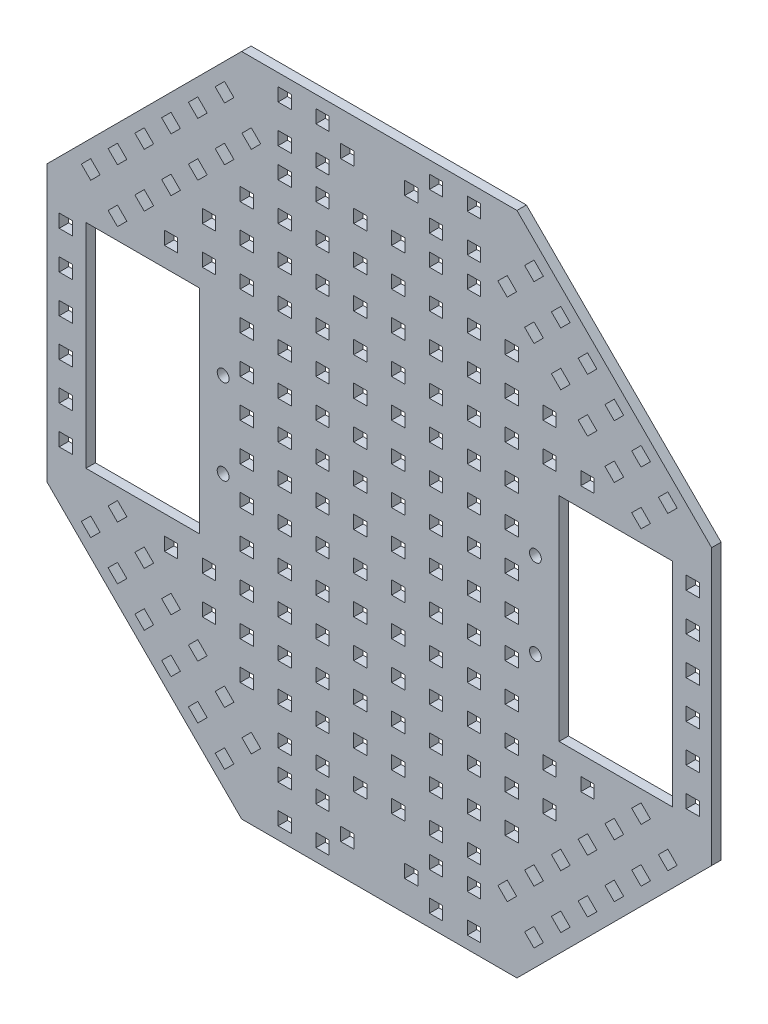
SolidWorks part; units mm, degrees
ref_plane "Plano frontal" through (0, 0, 0) normal (0, 0, 1) x (1, 0, 0)
ref_plane "Plano superior" through (0, 0, 0) normal (0, 1, 0) x (1, 0, 0)
ref_plane "Plano direito" through (0, 0, 0) normal (1, 0, 0) x (0, 0, -1)
sketch "Esboço1" plane through (0, 0, 0) normal (0, 0, 1) x (1, 0, 0)
  line L0 (-50, -22.5) -> (-38, -22.5)
  line L1 (-38, -22.5) -> (-38, 22.5)
  line L2 (-38, 22.5) -> (-50, 22.5)
  line L3 (-50, 22.5) -> (-50, 52.5)
  line L4 (-50, 52.5) -> (-35, 67.5)
  line L5 (-35, 67.5) -> (35, 67.5)
  line L6 (35, 67.5) -> (50, 52.5)
  line L7 (50, 52.5) -> (50, 22.5)
  line L8 (50, 22.5) -> (38, 22.5)
  line L9 (38, 22.5) -> (38, -22.5)
  line L10 (38, -22.5) -> (50, -22.5)
  line L11 (50, -22.5) -> (50, -27.5)
  line L12 (50, -27.5) -> (45, -32.5)
  line L13 (45, -32.5) -> (-45, -32.5)
  line L14 (-45, -32.5) -> (-50, -27.5)
  line L15 (-50, -27.5) -> (-50, -22.5)
  line L16 (-38, 0) -> (38, 0) construction
  line L17 (-33, -9) -> (-33, 0) construction
  line L18 (-33, 0) -> (-33, 9) construction
  line L19 (-33, 9) -> (-38, 9) construction
  line L20 (33.0001, -8.9993) -> (33.0001, 0) construction
  line L21 (33.0001, 0) -> (33, 8.9999) construction
  line L22 (33, 8.9999) -> (38, 8.9999) construction
  circle A0 centre (-33, -9) radius 1.25
  circle A1 centre (-33, 9) radius 1.25
  circle A2 centre (33.0001, -8.9993) radius 1.2496
  circle A3 centre (33, 8.9999) radius 1.2455
  circle A4 centre (-6.75, 62.5) radius 1.2455
  circle A5 centre (6.75, 62.5) radius 1.2455
  circle A6 centre (0, 0) radius 76.0345 construction
  point P54 (0, 0)
sketch "Esboço2" plane through (0, 0, 0) normal (0, 0, 1) x (1, 0, 0)
  line L0 (-50, -27.5) -> (-50, 52.5)
  line L1 (-50, 52.5) -> (-35, 67.5)
  line L2 (-35, 67.5) -> (35, 67.5)
  line L3 (35, 67.5) -> (50, 52.5)
  line L4 (50, 52.5) -> (50, -27.5)
  line L5 (50, -27.5) -> (45, -32.5)
  line L6 (45, -32.5) -> (-45, -32.5)
  line L7 (-45, -32.5) -> (-50, -27.5)
  circle A0 centre (-23.9727, 48.5782) radius 1.2483
  circle A1 centre (-20.797, -17.4645) radius 1.2455
  circle A2 centre (21.113, -17.4645) radius 1.25
  circle A3 centre (24.288, 48.5754) radius 1.25
  point P6 (-35, 67.5)
sketch "Esboço4" plane through (0, 0, 0) normal (0, 0, 1) x (1, 0, 0)
  line L0 (0, 0) -> (0, -50000) construction
  line L1 (-38, 0) -> (-38, 22.5)
  line L2 (29.0972, 70.2467) -> (-29.0972, 70.2467)
  line L3 (-29.0972, 70.2467) -> (-70.2467, 29.0972)
  line L4 (-70.2467, 29.0972) -> (-70.2467, -29.0972)
  line L5 (-70.2467, -29.0972) -> (-29.0972, -70.2467)
  line L6 (-29.0972, -70.2467) -> (29.0972, -70.2467)
  line L7 (-38, 0) -> (38, 0) construction
  line L8 (-8.15, -61.1) -> (-5.35, -63.9) construction
  line L9 (-8.15, -63.9) -> (-5.35, -61.1) construction
  line L10 (-38, 22.5) -> (-62, 22.5)
  line L11 (-62, 22.5) -> (-62, -22.5)
  line L12 (-62, -22.5) -> (-38, -22.5)
  line L13 (-38, -22.5) -> (-38, 0)
  line L14 (-5.35, -63.9) -> (-5.35, -61.1)
  line L15 (-8.15, 63.9) -> (-5.35, 63.9)
  line L16 (-8.15, 63.9) -> (-8.15, 61.1)
  line L17 (-8.15, 61.1) -> (-5.35, 61.1)
  line L18 (-5.35, 63.9) -> (-5.35, 61.1)
  line L19 (-8.15, 63.9) -> (-5.35, 61.1) construction
  line L20 (-8.15, 61.1) -> (-5.35, 63.9) construction
  line L21 (70.2467, -29.0972) -> (70.2467, 0) [skipped]
  line L22 (49.672, -49.672) -> (70.2467, -29.0972) [skipped]
  line L23 (70.2467, 29.0972) -> (29.0972, 70.2467) [skipped]
  line L24 (-8.15, -61.1) -> (-5.35, -61.1)
  line L25 (-8.15, -63.9) -> (-8.15, -61.1)
  line L26 (-8.15, -63.9) -> (-5.35, -63.9)
  line L27 (8.15, 61.1) -> (5.35, 63.9) construction
  line L28 (8.15, 63.9) -> (5.35, 61.1) construction
  line L29 (8.15, -63.9) -> (5.35, -61.1) construction
  line L30 (8.15, -61.1) -> (5.35, -63.9) construction
  line L31 (8.15, -63.9) -> (5.35, -63.9)
  line L32 (8.15, -63.9) -> (8.15, -61.1)
  line L33 (8.15, -61.1) -> (5.35, -61.1)
  line L34 (5.35, 63.9) -> (5.35, 61.1)
  line L35 (8.15, 61.1) -> (5.35, 61.1)
  line L36 (8.15, 63.9) -> (8.15, 61.1)
  line L37 (8.15, 63.9) -> (5.35, 63.9)
  line L38 (5.35, -63.9) -> (5.35, -61.1)
  line L39 (38, -22.5) -> (38, 0)
  line L40 (62, -22.5) -> (38, -22.5)
  line L41 (62, 22.5) -> (62, -22.5)
  line L42 (38, 22.5) -> (62, 22.5)
  line L43 (70.2467, -29.0972) -> (29.0972, -70.2467)
  line L44 (70.2467, 29.0972) -> (70.2467, -29.0972)
  line L45 (29.0972, 70.2467) -> (70.2467, 29.0972)
  line L46 (38, 0) -> (38, 22.5)
  circle A0 centre (0, 0) radius 76.0345 construction
  circle A1 centre (0, 0) radius 70.2467 construction
  circle A2 centre (-33, 9) radius 1.25
  circle A3 centre (-33, -9) radius 1.25
  circle A4 centre (33, -9) radius 1.25
  circle A5 centre (33, 9) radius 1.25
  point P1 (6.75, -62.5)
  point P30 (-6.75, 62.5)
  point P36 (-6.75, -62.5)
  point P63 (0, -70.2467)
  point P66 (0, 70.2467)
  point P67 (6.75, 62.5)
extrude "Ressalto-extrusão1" add sketch "Esboço4" along normal blind 2
sketch "Esboço5" plane through (0, 0, 0) normal (0, 0, -1) x (-1, 0, 0)
  line L0 (0, 0) -> (-4, 0) construction
  line L1 (-4, 0) -> (-4, -4) construction
  line L2 (-10.6, -5.4) -> (-13.4, -5.4)
  line L3 (-2.6, -5.4) -> (-5.4, -5.4)
  line L4 (-2.6, -5.4) -> (-2.6, -2.6)
  line L5 (-2.6, -2.6) -> (-5.4, -2.6)
  line L6 (-5.4, -5.4) -> (-5.4, -2.6)
  line L7 (-2.6, -5.4) -> (-5.4, -2.6) construction
  line L8 (-2.6, -2.6) -> (-5.4, -5.4) construction
  line L9 (-10.6, -5.4) -> (-10.6, -2.6)
  line L10 (-10.6, -2.6) -> (-13.4, -2.6)
  line L11 (-13.4, -5.4) -> (-13.4, -2.6)
  line L12 (-10.6, -5.4) -> (-13.4, -2.6) construction
  line L13 (-10.6, -2.6) -> (-13.4, -5.4) construction
  line L14 (-18.6, -5.4) -> (-21.4, -5.4)
  line L15 (-18.6, -5.4) -> (-18.6, -2.6)
  line L16 (-18.6, -2.6) -> (-21.4, -2.6)
  line L17 (-21.4, -5.4) -> (-21.4, -2.6)
  line L18 (-18.6, -5.4) -> (-21.4, -2.6) construction
  line L19 (-18.6, -2.6) -> (-21.4, -5.4) construction
  line L20 (-26.6, -5.4) -> (-29.4, -5.4)
  line L21 (-26.6, -5.4) -> (-26.6, -2.6)
  line L22 (-26.6, -2.6) -> (-29.4, -2.6)
  line L23 (-29.4, -5.4) -> (-29.4, -2.6)
  line L24 (-26.6, -5.4) -> (-29.4, -2.6) construction
  line L25 (-26.6, -2.6) -> (-29.4, -5.4) construction
  line L26 (-34.6, -5.4) -> (-37.4, -5.4) [skipped]
  line L27 (-34.6, -5.4) -> (-34.6, -2.6) [skipped]
  line L28 (-34.6, -2.6) -> (-37.4, -2.6) [skipped]
  line L29 (-37.4, -5.4) -> (-37.4, -2.6) [skipped]
  line L30 (-34.6, -5.4) -> (-37.4, -2.6) construction
  line L31 (-34.6, -2.6) -> (-37.4, -5.4) construction
  line L32 (-42.6, -5.4) -> (-45.4, -5.4) [skipped]
  line L33 (-42.6, -5.4) -> (-42.6, -2.6) [skipped]
  line L34 (-42.6, -2.6) -> (-45.4, -2.6) [skipped]
  line L35 (-45.4, -5.4) -> (-45.4, -2.6) [skipped]
  line L36 (-42.6, -5.4) -> (-45.4, -2.6) construction
  line L37 (-42.6, -2.6) -> (-45.4, -5.4) construction
  line L38 (-50.6, -5.4) -> (-53.4, -5.4) [skipped]
  line L39 (-50.6, -5.4) -> (-50.6, -2.6) [skipped]
  line L40 (-50.6, -2.6) -> (-53.4, -2.6) [skipped]
  line L41 (-53.4, -5.4) -> (-53.4, -2.6) [skipped]
  line L42 (-50.6, -5.4) -> (-53.4, -2.6) construction
  line L43 (-50.6, -2.6) -> (-53.4, -5.4) construction
  line L44 (-10.6, -13.4) -> (-13.4, -13.4)
  line L45 (-10.6, -13.4) -> (-10.6, -10.6)
  line L46 (-10.6, -10.6) -> (-13.4, -10.6)
  line L47 (-13.4, -13.4) -> (-13.4, -10.6)
  line L48 (-10.6, -13.4) -> (-13.4, -10.6) construction
  line L49 (-10.6, -10.6) -> (-13.4, -13.4) construction
  line L50 (-18.6, -13.4) -> (-21.4, -13.4)
  line L51 (-18.6, -13.4) -> (-18.6, -10.6)
  line L52 (-18.6, -10.6) -> (-21.4, -10.6)
  line L53 (-21.4, -13.4) -> (-21.4, -10.6)
  line L54 (-18.6, -13.4) -> (-21.4, -10.6) construction
  line L55 (-18.6, -10.6) -> (-21.4, -13.4) construction
  line L56 (-26.6, -13.4) -> (-29.4, -13.4)
  line L57 (-26.6, -13.4) -> (-26.6, -10.6)
  line L58 (-26.6, -10.6) -> (-29.4, -10.6)
  line L59 (-29.4, -13.4) -> (-29.4, -10.6)
  line L60 (-26.6, -13.4) -> (-29.4, -10.6) construction
  line L61 (-26.6, -10.6) -> (-29.4, -13.4) construction
  line L62 (-34.6, -13.4) -> (-37.4, -13.4) [skipped]
  line L63 (-34.6, -13.4) -> (-34.6, -10.6) [skipped]
  line L64 (-34.6, -10.6) -> (-37.4, -10.6) [skipped]
  line L65 (-37.4, -13.4) -> (-37.4, -10.6) [skipped]
  line L66 (-34.6, -13.4) -> (-37.4, -10.6) construction
  line L67 (-34.6, -10.6) -> (-37.4, -13.4) construction
  line L68 (-42.6, -13.4) -> (-45.4, -13.4) [skipped]
  line L69 (-42.6, -13.4) -> (-42.6, -10.6) [skipped]
  line L70 (-42.6, -10.6) -> (-45.4, -10.6) [skipped]
  line L71 (-45.4, -13.4) -> (-45.4, -10.6) [skipped]
  line L72 (-42.6, -13.4) -> (-45.4, -10.6) construction
  line L73 (-42.6, -10.6) -> (-45.4, -13.4) construction
  line L74 (-50.6, -13.4) -> (-53.4, -13.4) [skipped]
  line L75 (-50.6, -13.4) -> (-50.6, -10.6) [skipped]
  line L76 (-50.6, -10.6) -> (-53.4, -10.6) [skipped]
  line L77 (-53.4, -13.4) -> (-53.4, -10.6) [skipped]
  line L78 (-50.6, -13.4) -> (-53.4, -10.6) construction
  line L79 (-50.6, -10.6) -> (-53.4, -13.4) construction
  line L80 (-10.6, -21.4) -> (-13.4, -21.4)
  line L81 (-10.6, -21.4) -> (-10.6, -18.6)
  line L82 (-10.6, -18.6) -> (-13.4, -18.6)
  line L83 (-13.4, -21.4) -> (-13.4, -18.6)
  line L84 (-10.6, -21.4) -> (-13.4, -18.6) construction
  line L85 (-10.6, -18.6) -> (-13.4, -21.4) construction
  line L86 (-18.6, -21.4) -> (-21.4, -21.4)
  line L87 (-18.6, -21.4) -> (-18.6, -18.6)
  line L88 (-18.6, -18.6) -> (-21.4, -18.6)
  line L89 (-21.4, -21.4) -> (-21.4, -18.6)
  line L90 (-18.6, -21.4) -> (-21.4, -18.6) construction
  line L91 (-18.6, -18.6) -> (-21.4, -21.4) construction
  line L92 (-26.6, -21.4) -> (-29.4, -21.4)
  line L93 (-26.6, -21.4) -> (-26.6, -18.6)
  line L94 (-26.6, -18.6) -> (-29.4, -18.6)
  line L95 (-29.4, -21.4) -> (-29.4, -18.6)
  line L96 (-26.6, -21.4) -> (-29.4, -18.6) construction
  line L97 (-26.6, -18.6) -> (-29.4, -21.4) construction
  line L98 (-34.6, -21.4) -> (-37.4, -21.4) [skipped]
  line L99 (-34.6, -21.4) -> (-34.6, -18.6) [skipped]
  line L100 (-34.6, -18.6) -> (-37.4, -18.6) [skipped]
  line L101 (-37.4, -21.4) -> (-37.4, -18.6) [skipped]
  line L102 (-34.6, -21.4) -> (-37.4, -18.6) construction
  line L103 (-34.6, -18.6) -> (-37.4, -21.4) construction
  line L104 (-42.6, -21.4) -> (-45.4, -21.4) [skipped]
  line L105 (-42.6, -21.4) -> (-42.6, -18.6) [skipped]
  line L106 (-42.6, -18.6) -> (-45.4, -18.6) [skipped]
  line L107 (-45.4, -21.4) -> (-45.4, -18.6) [skipped]
  line L108 (-42.6, -21.4) -> (-45.4, -18.6) construction
  line L109 (-42.6, -18.6) -> (-45.4, -21.4) construction
  line L110 (-50.6, -21.4) -> (-53.4, -21.4) [skipped]
  line L111 (-50.6, -21.4) -> (-50.6, -18.6) [skipped]
  line L112 (-50.6, -18.6) -> (-53.4, -18.6) [skipped]
  line L113 (-53.4, -21.4) -> (-53.4, -18.6) [skipped]
  line L114 (-50.6, -21.4) -> (-53.4, -18.6) construction
  line L115 (-50.6, -18.6) -> (-53.4, -21.4) construction
  line L116 (-10.6, -29.4) -> (-13.4, -29.4)
  line L117 (-10.6, -29.4) -> (-10.6, -26.6)
  line L118 (-10.6, -26.6) -> (-13.4, -26.6)
  line L119 (-13.4, -29.4) -> (-13.4, -26.6)
  line L120 (-10.6, -29.4) -> (-13.4, -26.6) construction
  line L121 (-10.6, -26.6) -> (-13.4, -29.4) construction
  line L122 (-18.6, -29.4) -> (-21.4, -29.4)
  line L123 (-18.6, -29.4) -> (-18.6, -26.6)
  line L124 (-18.6, -26.6) -> (-21.4, -26.6)
  line L125 (-21.4, -29.4) -> (-21.4, -26.6)
  line L126 (-18.6, -29.4) -> (-21.4, -26.6) construction
  line L127 (-18.6, -26.6) -> (-21.4, -29.4) construction
  line L128 (-26.6, -29.4) -> (-29.4, -29.4)
  line L129 (-26.6, -29.4) -> (-26.6, -26.6)
  line L130 (-26.6, -26.6) -> (-29.4, -26.6)
  line L131 (-29.4, -29.4) -> (-29.4, -26.6)
  line L132 (-26.6, -29.4) -> (-29.4, -26.6) construction
  line L133 (-26.6, -26.6) -> (-29.4, -29.4) construction
  line L134 (-34.6, -29.4) -> (-37.4, -29.4)
  line L135 (-34.6, -29.4) -> (-34.6, -26.6)
  line L136 (-34.6, -26.6) -> (-37.4, -26.6)
  line L137 (-37.4, -29.4) -> (-37.4, -26.6)
  line L138 (-34.6, -29.4) -> (-37.4, -26.6) construction
  line L139 (-34.6, -26.6) -> (-37.4, -29.4) construction
  line L140 (-42.6, -29.4) -> (-45.4, -29.4)
  line L141 (-42.6, -29.4) -> (-42.6, -26.6)
  line L142 (-42.6, -26.6) -> (-45.4, -26.6)
  line L143 (-45.4, -29.4) -> (-45.4, -26.6)
  line L144 (-42.6, -29.4) -> (-45.4, -26.6) construction
  line L145 (-42.6, -26.6) -> (-45.4, -29.4) construction
  line L146 (-50.6, -29.4) -> (-53.4, -29.4) [skipped]
  line L147 (-50.6, -29.4) -> (-50.6, -26.6) [skipped]
  line L148 (-50.6, -26.6) -> (-53.4, -26.6) [skipped]
  line L149 (-53.4, -29.4) -> (-53.4, -26.6) [skipped]
  line L150 (-50.6, -29.4) -> (-53.4, -26.6) construction
  line L151 (-50.6, -26.6) -> (-53.4, -29.4) construction
  line L152 (-10.6, -37.4) -> (-13.4, -37.4)
  line L153 (-10.6, -37.4) -> (-10.6, -34.6)
  line L154 (-10.6, -34.6) -> (-13.4, -34.6)
  line L155 (-13.4, -37.4) -> (-13.4, -34.6)
  line L156 (-10.6, -37.4) -> (-13.4, -34.6) construction
  line L157 (-10.6, -34.6) -> (-13.4, -37.4) construction
  line L158 (-18.6, -37.4) -> (-21.4, -37.4)
  line L159 (-18.6, -37.4) -> (-18.6, -34.6)
  line L160 (-18.6, -34.6) -> (-21.4, -34.6)
  line L161 (-21.4, -37.4) -> (-21.4, -34.6)
  line L162 (-18.6, -37.4) -> (-21.4, -34.6) construction
  line L163 (-18.6, -34.6) -> (-21.4, -37.4) construction
  line L164 (-26.6, -37.4) -> (-29.4, -37.4)
  line L165 (-26.6, -37.4) -> (-26.6, -34.6)
  line L166 (-26.6, -34.6) -> (-29.4, -34.6)
  line L167 (-29.4, -37.4) -> (-29.4, -34.6)
  line L168 (-26.6, -37.4) -> (-29.4, -34.6) construction
  line L169 (-26.6, -34.6) -> (-29.4, -37.4) construction
  line L170 (-34.6, -37.4) -> (-37.4, -37.4)
  line L171 (-34.6, -37.4) -> (-34.6, -34.6)
  line L172 (-34.6, -34.6) -> (-37.4, -34.6)
  line L173 (-37.4, -37.4) -> (-37.4, -34.6)
  line L174 (-34.6, -37.4) -> (-37.4, -34.6) construction
  line L175 (-34.6, -34.6) -> (-37.4, -37.4) construction
  line L176 (-42.6, -37.4) -> (-45.4, -37.4) [skipped]
  line L177 (-42.6, -37.4) -> (-42.6, -34.6) [skipped]
  line L178 (-42.6, -34.6) -> (-45.4, -34.6) [skipped]
  line L179 (-45.4, -37.4) -> (-45.4, -34.6) [skipped]
  line L180 (-42.6, -37.4) -> (-45.4, -34.6) construction
  line L181 (-42.6, -34.6) -> (-45.4, -37.4) construction
  line L182 (-50.6, -37.4) -> (-53.4, -37.4) [skipped]
  line L183 (-50.6, -37.4) -> (-50.6, -34.6) [skipped]
  line L184 (-50.6, -34.6) -> (-53.4, -34.6) [skipped]
  line L185 (-53.4, -37.4) -> (-53.4, -34.6) [skipped]
  line L186 (-50.6, -37.4) -> (-53.4, -34.6) construction
  line L187 (-50.6, -34.6) -> (-53.4, -37.4) construction
  line L188 (-10.6, -45.4) -> (-13.4, -45.4)
  line L189 (-10.6, -45.4) -> (-10.6, -42.6)
  line L190 (-10.6, -42.6) -> (-13.4, -42.6)
  line L191 (-13.4, -45.4) -> (-13.4, -42.6)
  line L192 (-10.6, -45.4) -> (-13.4, -42.6) construction
  line L193 (-10.6, -42.6) -> (-13.4, -45.4) construction
  line L194 (-18.6, -45.4) -> (-21.4, -45.4)
  line L195 (-18.6, -45.4) -> (-18.6, -42.6)
  line L196 (-18.6, -42.6) -> (-21.4, -42.6)
  line L197 (-21.4, -45.4) -> (-21.4, -42.6)
  line L198 (-18.6, -45.4) -> (-21.4, -42.6) construction
  line L199 (-18.6, -42.6) -> (-21.4, -45.4) construction
  line L200 (-26.6, -45.4) -> (-29.4, -45.4)
  line L201 (-26.6, -45.4) -> (-26.6, -42.6)
  line L202 (-26.6, -42.6) -> (-29.4, -42.6)
  line L203 (-29.4, -45.4) -> (-29.4, -42.6)
  line L204 (-26.6, -45.4) -> (-29.4, -42.6) construction
  line L205 (-26.6, -42.6) -> (-29.4, -45.4) construction
  line L206 (-34.6, -45.4) -> (-37.4, -45.4) [skipped]
  line L207 (-34.6, -45.4) -> (-34.6, -42.6) [skipped]
  line L208 (-34.6, -42.6) -> (-37.4, -42.6) [skipped]
  line L209 (-37.4, -45.4) -> (-37.4, -42.6) [skipped]
  line L210 (-34.6, -45.4) -> (-37.4, -42.6) construction
  line L211 (-34.6, -42.6) -> (-37.4, -45.4) construction
  line L212 (-42.6, -45.4) -> (-45.4, -45.4) [skipped]
  line L213 (-42.6, -45.4) -> (-42.6, -42.6) [skipped]
  line L214 (-42.6, -42.6) -> (-45.4, -42.6) [skipped]
  line L215 (-45.4, -45.4) -> (-45.4, -42.6) [skipped]
  line L216 (-42.6, -45.4) -> (-45.4, -42.6) construction
  line L217 (-42.6, -42.6) -> (-45.4, -45.4) construction
  line L218 (-50.6, -45.4) -> (-53.4, -45.4) [skipped]
  line L219 (-50.6, -45.4) -> (-50.6, -42.6) [skipped]
  line L220 (-50.6, -42.6) -> (-53.4, -42.6) [skipped]
  line L221 (-53.4, -45.4) -> (-53.4, -42.6) [skipped]
  line L222 (-50.6, -45.4) -> (-53.4, -42.6) construction
  line L223 (-50.6, -42.6) -> (-53.4, -45.4) construction
  line L224 (-10.6, -53.4) -> (-13.4, -53.4)
  line L225 (-10.6, -53.4) -> (-10.6, -50.6)
  line L226 (-10.6, -50.6) -> (-13.4, -50.6)
  line L227 (-13.4, -53.4) -> (-13.4, -50.6)
  line L228 (-10.6, -53.4) -> (-13.4, -50.6) construction
  line L229 (-10.6, -50.6) -> (-13.4, -53.4) construction
  line L230 (-18.6, -53.4) -> (-21.4, -53.4)
  line L231 (-18.6, -53.4) -> (-18.6, -50.6)
  line L232 (-18.6, -50.6) -> (-21.4, -50.6)
  line L233 (-21.4, -53.4) -> (-21.4, -50.6)
  line L234 (-18.6, -53.4) -> (-21.4, -50.6) construction
  line L235 (-18.6, -50.6) -> (-21.4, -53.4) construction
  line L236 (-26.6, -53.4) -> (-29.4, -53.4) [skipped]
  line L237 (-26.6, -53.4) -> (-26.6, -50.6) [skipped]
  line L238 (-26.6, -50.6) -> (-29.4, -50.6) [skipped]
  line L239 (-29.4, -53.4) -> (-29.4, -50.6) [skipped]
  line L240 (-26.6, -53.4) -> (-29.4, -50.6) construction
  line L241 (-26.6, -50.6) -> (-29.4, -53.4) construction
  line L242 (-34.6, -53.4) -> (-37.4, -53.4) [skipped]
  line L243 (-34.6, -53.4) -> (-34.6, -50.6) [skipped]
  line L244 (-34.6, -50.6) -> (-37.4, -50.6) [skipped]
  line L245 (-37.4, -53.4) -> (-37.4, -50.6) [skipped]
  line L246 (-34.6, -53.4) -> (-37.4, -50.6) construction
  line L247 (-34.6, -50.6) -> (-37.4, -53.4) construction
  line L248 (-42.6, -53.4) -> (-45.4, -53.4) [skipped]
  line L249 (-42.6, -53.4) -> (-42.6, -50.6) [skipped]
  line L250 (-42.6, -50.6) -> (-45.4, -50.6) [skipped]
  line L251 (-45.4, -53.4) -> (-45.4, -50.6) [skipped]
  line L252 (-42.6, -53.4) -> (-45.4, -50.6) construction
  line L253 (-42.6, -50.6) -> (-45.4, -53.4) construction
  line L254 (2.6, -50.6) -> (5.4, -53.4) construction
  line L255 (2.6, -53.4) -> (5.4, -50.6) construction
  line L256 (2.6, -42.6) -> (5.4, -45.4) construction
  line L257 (2.6, -45.4) -> (5.4, -42.6) construction
  line L258 (2.6, -34.6) -> (5.4, -37.4) construction
  line L259 (2.6, -37.4) -> (5.4, -34.6) construction
  line L260 (-2.6, -13.4) -> (-5.4, -13.4)
  line L261 (-2.6, -13.4) -> (-2.6, -10.6)
  line L262 (-2.6, -10.6) -> (-5.4, -10.6)
  line L263 (-5.4, -13.4) -> (-5.4, -10.6)
  line L264 (-2.6, -13.4) -> (-5.4, -10.6) construction
  line L265 (-2.6, -10.6) -> (-5.4, -13.4) construction
  line L266 (-2.6, -21.4) -> (-5.4, -21.4)
  line L267 (-2.6, -21.4) -> (-2.6, -18.6)
  line L268 (-2.6, -18.6) -> (-5.4, -18.6)
  line L269 (-5.4, -21.4) -> (-5.4, -18.6)
  line L270 (-2.6, -21.4) -> (-5.4, -18.6) construction
  line L271 (-2.6, -18.6) -> (-5.4, -21.4) construction
  line L272 (-2.6, -29.4) -> (-5.4, -29.4)
  line L273 (-2.6, -29.4) -> (-2.6, -26.6)
  line L274 (-2.6, -26.6) -> (-5.4, -26.6)
  line L275 (-5.4, -29.4) -> (-5.4, -26.6)
  line L276 (-2.6, -29.4) -> (-5.4, -26.6) construction
  line L277 (-2.6, -26.6) -> (-5.4, -29.4) construction
  line L278 (-2.6, -37.4) -> (-5.4, -37.4)
  line L279 (-2.6, -37.4) -> (-2.6, -34.6)
  line L280 (-2.6, -34.6) -> (-5.4, -34.6)
  line L281 (-5.4, -37.4) -> (-5.4, -34.6)
  line L282 (-2.6, -37.4) -> (-5.4, -34.6) construction
  line L283 (-2.6, -34.6) -> (-5.4, -37.4) construction
  line L284 (-2.6, -45.4) -> (-5.4, -45.4)
  line L285 (-2.6, -45.4) -> (-2.6, -42.6)
  line L286 (-2.6, -42.6) -> (-5.4, -42.6)
  line L287 (-5.4, -45.4) -> (-5.4, -42.6)
  line L288 (-2.6, -45.4) -> (-5.4, -42.6) construction
  line L289 (-2.6, -42.6) -> (-5.4, -45.4) construction
  line L290 (-2.6, -53.4) -> (-5.4, -53.4)
  line L291 (-2.6, -53.4) -> (-2.6, -50.6)
  line L292 (-2.6, -50.6) -> (-5.4, -50.6)
  line L293 (-5.4, -53.4) -> (-5.4, -50.6)
  line L294 (-2.6, -53.4) -> (-5.4, -50.6) construction
  line L295 (-2.6, -50.6) -> (-5.4, -53.4) construction
  line L296 (0, 0) -> (0, -70.2467) construction
  line L297 (29.0972, -70.2467) -> (-29.0972, -70.2467) construction
  line L298 (0, 0) -> (-70.2467, 0) construction
  line L299 (-70.2467, -29.0972) -> (-70.2467, 29.0972) construction
  line L300 (2.6, -26.6) -> (5.4, -29.4) construction
  line L301 (-50.6, -53.4) -> (-53.4, -53.4) [skipped]
  line L302 (-50.6, -53.4) -> (-50.6, -50.6) [skipped]
  line L303 (-50.6, -50.6) -> (-53.4, -50.6) [skipped]
  line L304 (-53.4, -53.4) -> (-53.4, -50.6) [skipped]
  line L305 (-50.6, -53.4) -> (-53.4, -50.6) construction
  line L306 (-50.6, -50.6) -> (-53.4, -53.4) construction
  line L307 (2.6, -29.4) -> (5.4, -26.6) construction
  line L308 (2.6, -18.6) -> (5.4, -21.4) construction
  line L309 (2.6, -21.4) -> (5.4, -18.6) construction
  line L310 (2.6, -10.6) -> (5.4, -13.4) construction
  line L311 (2.6, -13.4) -> (5.4, -10.6) construction
  line L312 (18.6, -50.6) -> (21.4, -53.4) construction
  line L313 (18.6, -53.4) -> (21.4, -50.6) construction
  line L314 (10.6, -50.6) -> (13.4, -53.4) construction
  line L315 (10.6, -53.4) -> (13.4, -50.6) construction
  line L316 (26.6, -42.6) -> (29.4, -45.4) construction
  line L317 (26.6, -45.4) -> (29.4, -42.6) construction
  line L318 (18.6, -42.6) -> (21.4, -45.4) construction
  line L319 (18.6, -45.4) -> (21.4, -42.6) construction
  line L320 (10.6, -42.6) -> (13.4, -45.4) construction
  line L321 (10.6, -45.4) -> (13.4, -42.6) construction
  line L322 (34.6, -34.6) -> (37.4, -37.4) construction
  line L323 (34.6, -37.4) -> (37.4, -34.6) construction
  line L324 (26.6, -34.6) -> (29.4, -37.4) construction
  line L325 (26.6, -37.4) -> (29.4, -34.6) construction
  line L326 (18.6, -34.6) -> (21.4, -37.4) construction
  line L327 (18.6, -37.4) -> (21.4, -34.6) construction
  line L328 (10.6, -34.6) -> (13.4, -37.4) construction
  line L329 (10.6, -37.4) -> (13.4, -34.6) construction
  line L330 (42.6, -26.6) -> (45.4, -29.4) construction
  line L331 (42.6, -29.4) -> (45.4, -26.6) construction
  line L332 (34.6, -26.6) -> (37.4, -29.4) construction
  line L333 (34.6, -29.4) -> (37.4, -26.6) construction
  line L334 (26.6, -26.6) -> (29.4, -29.4) construction
  line L335 (26.6, -29.4) -> (29.4, -26.6) construction
  line L336 (18.6, -26.6) -> (21.4, -29.4) construction
  line L337 (18.6, -29.4) -> (21.4, -26.6) construction
  line L338 (10.6, -26.6) -> (13.4, -29.4) construction
  line L339 (10.6, -29.4) -> (13.4, -26.6) construction
  line L340 (26.6, -18.6) -> (29.4, -21.4) construction
  line L341 (26.6, -21.4) -> (29.4, -18.6) construction
  line L342 (18.6, -18.6) -> (21.4, -21.4) construction
  line L343 (18.6, -21.4) -> (21.4, -18.6) construction
  line L344 (10.6, -18.6) -> (13.4, -21.4) construction
  line L345 (10.6, -21.4) -> (13.4, -18.6) construction
  line L346 (26.6, -10.6) -> (29.4, -13.4) construction
  line L347 (26.6, -13.4) -> (29.4, -10.6) construction
  line L348 (18.6, -10.6) -> (21.4, -13.4) construction
  line L349 (18.6, -13.4) -> (21.4, -10.6) construction
  line L350 (10.6, -10.6) -> (13.4, -13.4) construction
  line L351 (10.6, -13.4) -> (13.4, -10.6) construction
  line L352 (26.6, -2.6) -> (29.4, -5.4) construction
  line L353 (26.6, -5.4) -> (29.4, -2.6) construction
  line L354 (18.6, -2.6) -> (21.4, -5.4) construction
  line L355 (18.6, -5.4) -> (21.4, -2.6) construction
  line L356 (10.6, -2.6) -> (13.4, -5.4) construction
  line L357 (10.6, -5.4) -> (13.4, -2.6) construction
  line L358 (2.6, -2.6) -> (5.4, -5.4) construction
  line L359 (2.6, -5.4) -> (5.4, -2.6) construction
  line L360 (5.4, -53.4) -> (5.4, -50.6)
  line L361 (2.6, -50.6) -> (5.4, -50.6)
  line L362 (2.6, -53.4) -> (2.6, -50.6)
  line L363 (2.6, -53.4) -> (5.4, -53.4)
  line L364 (5.4, -45.4) -> (5.4, -42.6)
  line L365 (2.6, -42.6) -> (5.4, -42.6)
  line L366 (2.6, -45.4) -> (2.6, -42.6)
  line L367 (2.6, -45.4) -> (5.4, -45.4)
  line L368 (5.4, -37.4) -> (5.4, -34.6)
  line L369 (2.6, -34.6) -> (5.4, -34.6)
  line L370 (2.6, -37.4) -> (2.6, -34.6)
  line L371 (2.6, -37.4) -> (5.4, -37.4)
  line L372 (5.4, -29.4) -> (5.4, -26.6)
  line L373 (2.6, -26.6) -> (5.4, -26.6)
  line L374 (2.6, -29.4) -> (2.6, -26.6)
  line L375 (2.6, -29.4) -> (5.4, -29.4)
  line L376 (5.4, -21.4) -> (5.4, -18.6)
  line L377 (2.6, -18.6) -> (5.4, -18.6)
  line L378 (2.6, -21.4) -> (2.6, -18.6)
  line L379 (2.6, -21.4) -> (5.4, -21.4)
  line L380 (5.4, -13.4) -> (5.4, -10.6)
  line L381 (2.6, -10.6) -> (5.4, -10.6)
  line L382 (2.6, -13.4) -> (2.6, -10.6)
  line L383 (2.6, -13.4) -> (5.4, -13.4)
  line L384 (21.4, -53.4) -> (21.4, -50.6)
  line L385 (18.6, -50.6) -> (21.4, -50.6)
  line L386 (18.6, -53.4) -> (18.6, -50.6)
  line L387 (18.6, -53.4) -> (21.4, -53.4)
  line L388 (13.4, -53.4) -> (13.4, -50.6)
  line L389 (10.6, -50.6) -> (13.4, -50.6)
  line L390 (10.6, -53.4) -> (10.6, -50.6)
  line L391 (10.6, -53.4) -> (13.4, -53.4)
  line L392 (29.4, -45.4) -> (29.4, -42.6)
  line L393 (26.6, -42.6) -> (29.4, -42.6)
  line L394 (26.6, -45.4) -> (26.6, -42.6)
  line L395 (26.6, -45.4) -> (29.4, -45.4)
  line L396 (21.4, -45.4) -> (21.4, -42.6)
  line L397 (18.6, -42.6) -> (21.4, -42.6)
  line L398 (18.6, -45.4) -> (18.6, -42.6)
  line L399 (18.6, -45.4) -> (21.4, -45.4)
  line L400 (13.4, -45.4) -> (13.4, -42.6)
  line L401 (10.6, -42.6) -> (13.4, -42.6)
  line L402 (10.6, -45.4) -> (10.6, -42.6)
  line L403 (10.6, -45.4) -> (13.4, -45.4)
  line L404 (37.4, -37.4) -> (37.4, -34.6)
  line L405 (34.6, -34.6) -> (37.4, -34.6)
  line L406 (34.6, -37.4) -> (34.6, -34.6)
  line L407 (34.6, -37.4) -> (37.4, -37.4)
  line L408 (29.4, -37.4) -> (29.4, -34.6)
  line L409 (26.6, -34.6) -> (29.4, -34.6)
  line L410 (26.6, -37.4) -> (26.6, -34.6)
  line L411 (26.6, -37.4) -> (29.4, -37.4)
  line L412 (21.4, -37.4) -> (21.4, -34.6)
  line L413 (18.6, -34.6) -> (21.4, -34.6)
  line L414 (18.6, -37.4) -> (18.6, -34.6)
  line L415 (18.6, -37.4) -> (21.4, -37.4)
  line L416 (13.4, -37.4) -> (13.4, -34.6)
  line L417 (10.6, -34.6) -> (13.4, -34.6)
  line L418 (10.6, -37.4) -> (10.6, -34.6)
  line L419 (10.6, -37.4) -> (13.4, -37.4)
  line L420 (45.4, -29.4) -> (45.4, -26.6)
  line L421 (42.6, -26.6) -> (45.4, -26.6)
  line L422 (42.6, -29.4) -> (42.6, -26.6)
  line L423 (42.6, -29.4) -> (45.4, -29.4)
  line L424 (37.4, -29.4) -> (37.4, -26.6)
  line L425 (34.6, -26.6) -> (37.4, -26.6)
  line L426 (34.6, -29.4) -> (34.6, -26.6)
  line L427 (34.6, -29.4) -> (37.4, -29.4)
  line L428 (29.4, -29.4) -> (29.4, -26.6)
  line L429 (26.6, -26.6) -> (29.4, -26.6)
  line L430 (26.6, -29.4) -> (26.6, -26.6)
  line L431 (26.6, -29.4) -> (29.4, -29.4)
  line L432 (21.4, -29.4) -> (21.4, -26.6)
  line L433 (18.6, -26.6) -> (21.4, -26.6)
  line L434 (18.6, -29.4) -> (18.6, -26.6)
  line L435 (18.6, -29.4) -> (21.4, -29.4)
  line L436 (13.4, -29.4) -> (13.4, -26.6)
  line L437 (10.6, -26.6) -> (13.4, -26.6)
  line L438 (10.6, -29.4) -> (10.6, -26.6)
  line L439 (10.6, -29.4) -> (13.4, -29.4)
  line L440 (29.4, -21.4) -> (29.4, -18.6)
  line L441 (26.6, -18.6) -> (29.4, -18.6)
  line L442 (26.6, -21.4) -> (26.6, -18.6)
  line L443 (26.6, -21.4) -> (29.4, -21.4)
  line L444 (21.4, -21.4) -> (21.4, -18.6)
  line L445 (18.6, -18.6) -> (21.4, -18.6)
  line L446 (18.6, -21.4) -> (18.6, -18.6)
  line L447 (18.6, -21.4) -> (21.4, -21.4)
  line L448 (13.4, -21.4) -> (13.4, -18.6)
  line L449 (10.6, -18.6) -> (13.4, -18.6)
  line L450 (10.6, -21.4) -> (10.6, -18.6)
  line L451 (10.6, -21.4) -> (13.4, -21.4)
  line L452 (29.4, -13.4) -> (29.4, -10.6)
  line L453 (26.6, -10.6) -> (29.4, -10.6)
  line L454 (26.6, -13.4) -> (26.6, -10.6)
  line L455 (26.6, -13.4) -> (29.4, -13.4)
  line L456 (21.4, -13.4) -> (21.4, -10.6)
  line L457 (18.6, -10.6) -> (21.4, -10.6)
  line L458 (18.6, -13.4) -> (18.6, -10.6)
  line L459 (18.6, -13.4) -> (21.4, -13.4)
  line L460 (13.4, -13.4) -> (13.4, -10.6)
  line L461 (10.6, -10.6) -> (13.4, -10.6)
  line L462 (10.6, -13.4) -> (10.6, -10.6)
  line L463 (10.6, -13.4) -> (13.4, -13.4)
  line L464 (29.4, -5.4) -> (29.4, -2.6)
  line L465 (26.6, -2.6) -> (29.4, -2.6)
  line L466 (26.6, -5.4) -> (26.6, -2.6)
  line L467 (26.6, -5.4) -> (29.4, -5.4)
  line L468 (21.4, -5.4) -> (21.4, -2.6)
  line L469 (18.6, -2.6) -> (21.4, -2.6)
  line L470 (18.6, -5.4) -> (18.6, -2.6)
  line L471 (18.6, -5.4) -> (21.4, -5.4)
  line L472 (13.4, -5.4) -> (13.4, -2.6)
  line L473 (10.6, -2.6) -> (13.4, -2.6)
  line L474 (10.6, -5.4) -> (10.6, -2.6)
  line L475 (5.4, -5.4) -> (5.4, -2.6)
  line L476 (2.6, -2.6) -> (5.4, -2.6)
  line L477 (2.6, -5.4) -> (2.6, -2.6)
  line L478 (2.6, -5.4) -> (5.4, -5.4)
  line L479 (10.6, -5.4) -> (13.4, -5.4)
  line L480 (2.6, 5.4) -> (5.4, 2.6) construction
  line L481 (2.6, 2.6) -> (5.4, 5.4) construction
  line L482 (10.6, 5.4) -> (13.4, 2.6) construction
  line L483 (10.6, 2.6) -> (13.4, 5.4) construction
  line L484 (18.6, 5.4) -> (21.4, 2.6) construction
  line L485 (18.6, 2.6) -> (21.4, 5.4) construction
  line L486 (26.6, 5.4) -> (29.4, 2.6) construction
  line L487 (26.6, 2.6) -> (29.4, 5.4) construction
  line L488 (10.6, 13.4) -> (13.4, 10.6) construction
  line L489 (10.6, 10.6) -> (13.4, 13.4) construction
  line L490 (18.6, 13.4) -> (21.4, 10.6) construction
  line L491 (18.6, 10.6) -> (21.4, 13.4) construction
  line L492 (26.6, 13.4) -> (29.4, 10.6) construction
  line L493 (26.6, 10.6) -> (29.4, 13.4) construction
  line L494 (10.6, 21.4) -> (13.4, 18.6) construction
  line L495 (10.6, 18.6) -> (13.4, 21.4) construction
  line L496 (18.6, 21.4) -> (21.4, 18.6) construction
  line L497 (18.6, 18.6) -> (21.4, 21.4) construction
  line L498 (26.6, 21.4) -> (29.4, 18.6) construction
  line L499 (26.6, 18.6) -> (29.4, 21.4) construction
  line L500 (10.6, 29.4) -> (13.4, 26.6) construction
  line L501 (10.6, 26.6) -> (13.4, 29.4) construction
  line L502 (18.6, 29.4) -> (21.4, 26.6) construction
  line L503 (18.6, 26.6) -> (21.4, 29.4) construction
  line L504 (26.6, 29.4) -> (29.4, 26.6) construction
  line L505 (26.6, 26.6) -> (29.4, 29.4) construction
  line L506 (34.6, 29.4) -> (37.4, 26.6) construction
  line L507 (34.6, 26.6) -> (37.4, 29.4) construction
  line L508 (42.6, 29.4) -> (45.4, 26.6) construction
  line L509 (42.6, 26.6) -> (45.4, 29.4) construction
  line L510 (10.6, 37.4) -> (13.4, 34.6) construction
  line L511 (10.6, 34.6) -> (13.4, 37.4) construction
  line L512 (18.6, 37.4) -> (21.4, 34.6) construction
  line L513 (18.6, 34.6) -> (21.4, 37.4) construction
  line L514 (26.6, 37.4) -> (29.4, 34.6) construction
  line L515 (26.6, 34.6) -> (29.4, 37.4) construction
  line L516 (34.6, 37.4) -> (37.4, 34.6) construction
  line L517 (34.6, 34.6) -> (37.4, 37.4) construction
  line L518 (10.6, 45.4) -> (13.4, 42.6) construction
  line L519 (10.6, 42.6) -> (13.4, 45.4) construction
  line L520 (18.6, 45.4) -> (21.4, 42.6) construction
  line L521 (18.6, 42.6) -> (21.4, 45.4) construction
  line L522 (26.6, 45.4) -> (29.4, 42.6) construction
  line L523 (26.6, 42.6) -> (29.4, 45.4) construction
  line L524 (10.6, 53.4) -> (13.4, 50.6) construction
  line L525 (10.6, 50.6) -> (13.4, 53.4) construction
  line L526 (18.6, 53.4) -> (21.4, 50.6) construction
  line L527 (18.6, 50.6) -> (21.4, 53.4) construction
  line L528 (2.6, 13.4) -> (5.4, 10.6) construction
  line L529 (2.6, 10.6) -> (5.4, 13.4) construction
  line L530 (2.6, 21.4) -> (5.4, 18.6) construction
  line L531 (2.6, 18.6) -> (5.4, 21.4) construction
  line L532 (2.6, 29.4) -> (5.4, 26.6) construction
  line L533 (2.6, 26.6) -> (5.4, 29.4) construction
  line L534 (-2.6, 50.6) -> (-5.4, 53.4) construction
  line L535 (-2.6, 53.4) -> (-5.4, 50.6) construction
  line L536 (-2.6, 42.6) -> (-5.4, 45.4) construction
  line L537 (-2.6, 45.4) -> (-5.4, 42.6) construction
  line L538 (-2.6, 34.6) -> (-5.4, 37.4) construction
  line L539 (-2.6, 37.4) -> (-5.4, 34.6) construction
  line L540 (-2.6, 26.6) -> (-5.4, 29.4) construction
  line L541 (-2.6, 29.4) -> (-5.4, 26.6) construction
  line L542 (-2.6, 18.6) -> (-5.4, 21.4) construction
  line L543 (-2.6, 21.4) -> (-5.4, 18.6) construction
  line L544 (-2.6, 10.6) -> (-5.4, 13.4) construction
  line L545 (-2.6, 13.4) -> (-5.4, 10.6) construction
  line L546 (2.6, 37.4) -> (5.4, 34.6) construction
  line L547 (2.6, 34.6) -> (5.4, 37.4) construction
  line L548 (2.6, 45.4) -> (5.4, 42.6) construction
  line L549 (2.6, 42.6) -> (5.4, 45.4) construction
  line L550 (2.6, 53.4) -> (5.4, 50.6) construction
  line L551 (2.6, 50.6) -> (5.4, 53.4) construction
  line L552 (-18.6, 50.6) -> (-21.4, 53.4) construction
  line L553 (-18.6, 53.4) -> (-21.4, 50.6) construction
  line L554 (-10.6, 50.6) -> (-13.4, 53.4) construction
  line L555 (-10.6, 53.4) -> (-13.4, 50.6) construction
  line L556 (-26.6, 42.6) -> (-29.4, 45.4) construction
  line L557 (-26.6, 45.4) -> (-29.4, 42.6) construction
  line L558 (-18.6, 42.6) -> (-21.4, 45.4) construction
  line L559 (-18.6, 45.4) -> (-21.4, 42.6) construction
  line L560 (-10.6, 42.6) -> (-13.4, 45.4) construction
  line L561 (-10.6, 45.4) -> (-13.4, 42.6) construction
  line L562 (-34.6, 34.6) -> (-37.4, 37.4) construction
  line L563 (-34.6, 37.4) -> (-37.4, 34.6) construction
  line L564 (-26.6, 34.6) -> (-29.4, 37.4) construction
  line L565 (-26.6, 37.4) -> (-29.4, 34.6) construction
  line L566 (-18.6, 34.6) -> (-21.4, 37.4) construction
  line L567 (-18.6, 37.4) -> (-21.4, 34.6) construction
  line L568 (-10.6, 34.6) -> (-13.4, 37.4) construction
  line L569 (-10.6, 37.4) -> (-13.4, 34.6) construction
  line L570 (-42.6, 26.6) -> (-45.4, 29.4) construction
  line L571 (-42.6, 29.4) -> (-45.4, 26.6) construction
  line L572 (-34.6, 26.6) -> (-37.4, 29.4) construction
  line L573 (-34.6, 29.4) -> (-37.4, 26.6) construction
  line L574 (-26.6, 26.6) -> (-29.4, 29.4) construction
  line L575 (-26.6, 29.4) -> (-29.4, 26.6) construction
  line L576 (-18.6, 26.6) -> (-21.4, 29.4) construction
  line L577 (-18.6, 29.4) -> (-21.4, 26.6) construction
  line L578 (-10.6, 26.6) -> (-13.4, 29.4) construction
  line L579 (-10.6, 29.4) -> (-13.4, 26.6) construction
  line L580 (-26.6, 18.6) -> (-29.4, 21.4) construction
  line L581 (-26.6, 21.4) -> (-29.4, 18.6) construction
  line L582 (-18.6, 18.6) -> (-21.4, 21.4) construction
  line L583 (-18.6, 21.4) -> (-21.4, 18.6) construction
  line L584 (-10.6, 18.6) -> (-13.4, 21.4) construction
  line L585 (-10.6, 21.4) -> (-13.4, 18.6) construction
  line L586 (-26.6, 10.6) -> (-29.4, 13.4) construction
  line L587 (-26.6, 13.4) -> (-29.4, 10.6) construction
  line L588 (-18.6, 10.6) -> (-21.4, 13.4) construction
  line L589 (-18.6, 13.4) -> (-21.4, 10.6) construction
  line L590 (-10.6, 10.6) -> (-13.4, 13.4) construction
  line L591 (-10.6, 13.4) -> (-13.4, 10.6) construction
  line L592 (-26.6, 2.6) -> (-29.4, 5.4) construction
  line L593 (-26.6, 5.4) -> (-29.4, 2.6) construction
  line L594 (-18.6, 2.6) -> (-21.4, 5.4) construction
  line L595 (-18.6, 5.4) -> (-21.4, 2.6) construction
  line L596 (-10.6, 2.6) -> (-13.4, 5.4) construction
  line L597 (-10.6, 5.4) -> (-13.4, 2.6) construction
  line L598 (-2.6, 2.6) -> (-5.4, 5.4) construction
  line L599 (-2.6, 5.4) -> (-5.4, 2.6) construction
  line L600 (10.6, 5.4) -> (13.4, 5.4)
  line L601 (2.6, 5.4) -> (5.4, 5.4)
  line L602 (2.6, 5.4) -> (2.6, 2.6)
  line L603 (2.6, 2.6) -> (5.4, 2.6)
  line L604 (5.4, 5.4) -> (5.4, 2.6)
  line L605 (10.6, 5.4) -> (10.6, 2.6)
  line L606 (10.6, 2.6) -> (13.4, 2.6)
  line L607 (13.4, 5.4) -> (13.4, 2.6)
  line L608 (18.6, 5.4) -> (21.4, 5.4)
  line L609 (18.6, 5.4) -> (18.6, 2.6)
  line L610 (18.6, 2.6) -> (21.4, 2.6)
  line L611 (21.4, 5.4) -> (21.4, 2.6)
  line L612 (26.6, 5.4) -> (29.4, 5.4)
  line L613 (26.6, 5.4) -> (26.6, 2.6)
  line L614 (26.6, 2.6) -> (29.4, 2.6)
  line L615 (29.4, 5.4) -> (29.4, 2.6)
  line L616 (10.6, 13.4) -> (13.4, 13.4)
  line L617 (10.6, 13.4) -> (10.6, 10.6)
  line L618 (10.6, 10.6) -> (13.4, 10.6)
  line L619 (13.4, 13.4) -> (13.4, 10.6)
  line L620 (18.6, 13.4) -> (21.4, 13.4)
  line L621 (18.6, 13.4) -> (18.6, 10.6)
  line L622 (18.6, 10.6) -> (21.4, 10.6)
  line L623 (21.4, 13.4) -> (21.4, 10.6)
  line L624 (26.6, 13.4) -> (29.4, 13.4)
  line L625 (26.6, 13.4) -> (26.6, 10.6)
  line L626 (26.6, 10.6) -> (29.4, 10.6)
  line L627 (29.4, 13.4) -> (29.4, 10.6)
  line L628 (10.6, 21.4) -> (13.4, 21.4)
  line L629 (10.6, 21.4) -> (10.6, 18.6)
  line L630 (10.6, 18.6) -> (13.4, 18.6)
  line L631 (13.4, 21.4) -> (13.4, 18.6)
  line L632 (18.6, 21.4) -> (21.4, 21.4)
  line L633 (18.6, 21.4) -> (18.6, 18.6)
  line L634 (18.6, 18.6) -> (21.4, 18.6)
  line L635 (21.4, 21.4) -> (21.4, 18.6)
  line L636 (26.6, 21.4) -> (29.4, 21.4)
  line L637 (26.6, 21.4) -> (26.6, 18.6)
  line L638 (26.6, 18.6) -> (29.4, 18.6)
  line L639 (29.4, 21.4) -> (29.4, 18.6)
  line L640 (10.6, 29.4) -> (13.4, 29.4)
  line L641 (10.6, 29.4) -> (10.6, 26.6)
  line L642 (10.6, 26.6) -> (13.4, 26.6)
  line L643 (13.4, 29.4) -> (13.4, 26.6)
  line L644 (18.6, 29.4) -> (21.4, 29.4)
  line L645 (18.6, 29.4) -> (18.6, 26.6)
  line L646 (18.6, 26.6) -> (21.4, 26.6)
  line L647 (21.4, 29.4) -> (21.4, 26.6)
  line L648 (26.6, 29.4) -> (29.4, 29.4)
  line L649 (26.6, 29.4) -> (26.6, 26.6)
  line L650 (26.6, 26.6) -> (29.4, 26.6)
  line L651 (29.4, 29.4) -> (29.4, 26.6)
  line L652 (34.6, 29.4) -> (37.4, 29.4)
  line L653 (34.6, 29.4) -> (34.6, 26.6)
  line L654 (34.6, 26.6) -> (37.4, 26.6)
  line L655 (37.4, 29.4) -> (37.4, 26.6)
  line L656 (42.6, 29.4) -> (45.4, 29.4)
  line L657 (42.6, 29.4) -> (42.6, 26.6)
  line L658 (42.6, 26.6) -> (45.4, 26.6)
  line L659 (45.4, 29.4) -> (45.4, 26.6)
  line L660 (10.6, 37.4) -> (13.4, 37.4)
  line L661 (10.6, 37.4) -> (10.6, 34.6)
  line L662 (10.6, 34.6) -> (13.4, 34.6)
  line L663 (13.4, 37.4) -> (13.4, 34.6)
  line L664 (18.6, 37.4) -> (21.4, 37.4)
  line L665 (18.6, 37.4) -> (18.6, 34.6)
  line L666 (18.6, 34.6) -> (21.4, 34.6)
  line L667 (21.4, 37.4) -> (21.4, 34.6)
  line L668 (26.6, 37.4) -> (29.4, 37.4)
  line L669 (26.6, 37.4) -> (26.6, 34.6)
  line L670 (26.6, 34.6) -> (29.4, 34.6)
  line L671 (29.4, 37.4) -> (29.4, 34.6)
  line L672 (34.6, 37.4) -> (37.4, 37.4)
  line L673 (34.6, 37.4) -> (34.6, 34.6)
  line L674 (34.6, 34.6) -> (37.4, 34.6)
  line L675 (37.4, 37.4) -> (37.4, 34.6)
  line L676 (10.6, 45.4) -> (13.4, 45.4)
  line L677 (10.6, 45.4) -> (10.6, 42.6)
  line L678 (10.6, 42.6) -> (13.4, 42.6)
  line L679 (13.4, 45.4) -> (13.4, 42.6)
  line L680 (18.6, 45.4) -> (21.4, 45.4)
  line L681 (18.6, 45.4) -> (18.6, 42.6)
  line L682 (18.6, 42.6) -> (21.4, 42.6)
  line L683 (21.4, 45.4) -> (21.4, 42.6)
  line L684 (26.6, 45.4) -> (29.4, 45.4)
  line L685 (26.6, 45.4) -> (26.6, 42.6)
  line L686 (26.6, 42.6) -> (29.4, 42.6)
  line L687 (29.4, 45.4) -> (29.4, 42.6)
  line L688 (10.6, 53.4) -> (13.4, 53.4)
  line L689 (10.6, 53.4) -> (10.6, 50.6)
  line L690 (10.6, 50.6) -> (13.4, 50.6)
  line L691 (13.4, 53.4) -> (13.4, 50.6)
  line L692 (18.6, 53.4) -> (21.4, 53.4)
  line L693 (18.6, 53.4) -> (18.6, 50.6)
  line L694 (18.6, 50.6) -> (21.4, 50.6)
  line L695 (21.4, 53.4) -> (21.4, 50.6)
  line L696 (2.6, 13.4) -> (5.4, 13.4)
  line L697 (2.6, 13.4) -> (2.6, 10.6)
  line L698 (2.6, 10.6) -> (5.4, 10.6)
  line L699 (5.4, 13.4) -> (5.4, 10.6)
  line L700 (2.6, 21.4) -> (5.4, 21.4)
  line L701 (2.6, 21.4) -> (2.6, 18.6)
  line L702 (2.6, 18.6) -> (5.4, 18.6)
  line L703 (5.4, 21.4) -> (5.4, 18.6)
  line L704 (2.6, 29.4) -> (5.4, 29.4)
  line L705 (2.6, 29.4) -> (2.6, 26.6)
  line L706 (2.6, 26.6) -> (5.4, 26.6)
  line L707 (5.4, 29.4) -> (5.4, 26.6)
  line L708 (2.6, 37.4) -> (5.4, 37.4)
  line L709 (2.6, 37.4) -> (2.6, 34.6)
  line L710 (2.6, 34.6) -> (5.4, 34.6)
  line L711 (5.4, 37.4) -> (5.4, 34.6)
  line L712 (2.6, 45.4) -> (5.4, 45.4)
  line L713 (2.6, 45.4) -> (2.6, 42.6)
  line L714 (2.6, 42.6) -> (5.4, 42.6)
  line L715 (5.4, 45.4) -> (5.4, 42.6)
  line L716 (2.6, 53.4) -> (5.4, 53.4)
  line L717 (2.6, 53.4) -> (2.6, 50.6)
  line L718 (2.6, 50.6) -> (5.4, 50.6)
  line L719 (5.4, 53.4) -> (5.4, 50.6)
  line L720 (-5.4, 53.4) -> (-5.4, 50.6)
  line L721 (-2.6, 50.6) -> (-5.4, 50.6)
  line L722 (-2.6, 53.4) -> (-2.6, 50.6)
  line L723 (-2.6, 53.4) -> (-5.4, 53.4)
  line L724 (-5.4, 45.4) -> (-5.4, 42.6)
  line L725 (-2.6, 42.6) -> (-5.4, 42.6)
  line L726 (-2.6, 45.4) -> (-2.6, 42.6)
  line L727 (-2.6, 45.4) -> (-5.4, 45.4)
  line L728 (-5.4, 37.4) -> (-5.4, 34.6)
  line L729 (-2.6, 34.6) -> (-5.4, 34.6)
  line L730 (-2.6, 37.4) -> (-2.6, 34.6)
  line L731 (-2.6, 37.4) -> (-5.4, 37.4)
  line L732 (-5.4, 29.4) -> (-5.4, 26.6)
  line L733 (-2.6, 26.6) -> (-5.4, 26.6)
  line L734 (-2.6, 29.4) -> (-2.6, 26.6)
  line L735 (-2.6, 29.4) -> (-5.4, 29.4)
  line L736 (-5.4, 21.4) -> (-5.4, 18.6)
  line L737 (-2.6, 18.6) -> (-5.4, 18.6)
  line L738 (-2.6, 21.4) -> (-2.6, 18.6)
  line L739 (-2.6, 21.4) -> (-5.4, 21.4)
  line L740 (-5.4, 13.4) -> (-5.4, 10.6)
  line L741 (-2.6, 10.6) -> (-5.4, 10.6)
  line L742 (-2.6, 13.4) -> (-2.6, 10.6)
  line L743 (-2.6, 13.4) -> (-5.4, 13.4)
  line L744 (-21.4, 53.4) -> (-21.4, 50.6)
  line L745 (-18.6, 50.6) -> (-21.4, 50.6)
  line L746 (-18.6, 53.4) -> (-18.6, 50.6)
  line L747 (-18.6, 53.4) -> (-21.4, 53.4)
  line L748 (-13.4, 53.4) -> (-13.4, 50.6)
  line L749 (-10.6, 50.6) -> (-13.4, 50.6)
  line L750 (-10.6, 53.4) -> (-10.6, 50.6)
  line L751 (-10.6, 53.4) -> (-13.4, 53.4)
  line L752 (-29.4, 45.4) -> (-29.4, 42.6)
  line L753 (-26.6, 42.6) -> (-29.4, 42.6)
  line L754 (-26.6, 45.4) -> (-26.6, 42.6)
  line L755 (-26.6, 45.4) -> (-29.4, 45.4)
  line L756 (-21.4, 45.4) -> (-21.4, 42.6)
  line L757 (-18.6, 42.6) -> (-21.4, 42.6)
  line L758 (-18.6, 45.4) -> (-18.6, 42.6)
  line L759 (-18.6, 45.4) -> (-21.4, 45.4)
  line L760 (-13.4, 45.4) -> (-13.4, 42.6)
  line L761 (-10.6, 42.6) -> (-13.4, 42.6)
  line L762 (-10.6, 45.4) -> (-10.6, 42.6)
  line L763 (-10.6, 45.4) -> (-13.4, 45.4)
  line L764 (-37.4, 37.4) -> (-37.4, 34.6)
  line L765 (-34.6, 34.6) -> (-37.4, 34.6)
  line L766 (-34.6, 37.4) -> (-34.6, 34.6)
  line L767 (-34.6, 37.4) -> (-37.4, 37.4)
  line L768 (-29.4, 37.4) -> (-29.4, 34.6)
  line L769 (-26.6, 34.6) -> (-29.4, 34.6)
  line L770 (-26.6, 37.4) -> (-26.6, 34.6)
  line L771 (-26.6, 37.4) -> (-29.4, 37.4)
  line L772 (-21.4, 37.4) -> (-21.4, 34.6)
  line L773 (-18.6, 34.6) -> (-21.4, 34.6)
  line L774 (-18.6, 37.4) -> (-18.6, 34.6)
  line L775 (-18.6, 37.4) -> (-21.4, 37.4)
  line L776 (-13.4, 37.4) -> (-13.4, 34.6)
  line L777 (-10.6, 34.6) -> (-13.4, 34.6)
  line L778 (-10.6, 37.4) -> (-10.6, 34.6)
  line L779 (-10.6, 37.4) -> (-13.4, 37.4)
  line L780 (-45.4, 29.4) -> (-45.4, 26.6)
  line L781 (-42.6, 26.6) -> (-45.4, 26.6)
  line L782 (-42.6, 29.4) -> (-42.6, 26.6)
  line L783 (-42.6, 29.4) -> (-45.4, 29.4)
  line L784 (-37.4, 29.4) -> (-37.4, 26.6)
  line L785 (-34.6, 26.6) -> (-37.4, 26.6)
  line L786 (-34.6, 29.4) -> (-34.6, 26.6)
  line L787 (-34.6, 29.4) -> (-37.4, 29.4)
  line L788 (-29.4, 29.4) -> (-29.4, 26.6)
  line L789 (-26.6, 26.6) -> (-29.4, 26.6)
  line L790 (-26.6, 29.4) -> (-26.6, 26.6)
  line L791 (-26.6, 29.4) -> (-29.4, 29.4)
  line L792 (-21.4, 29.4) -> (-21.4, 26.6)
  line L793 (-18.6, 26.6) -> (-21.4, 26.6)
  line L794 (-18.6, 29.4) -> (-18.6, 26.6)
  line L795 (-18.6, 29.4) -> (-21.4, 29.4)
  line L796 (-13.4, 29.4) -> (-13.4, 26.6)
  line L797 (-10.6, 26.6) -> (-13.4, 26.6)
  line L798 (-10.6, 29.4) -> (-10.6, 26.6)
  line L799 (-10.6, 29.4) -> (-13.4, 29.4)
  line L800 (-29.4, 21.4) -> (-29.4, 18.6)
  line L801 (-26.6, 18.6) -> (-29.4, 18.6)
  line L802 (-26.6, 21.4) -> (-26.6, 18.6)
  line L803 (-26.6, 21.4) -> (-29.4, 21.4)
  line L804 (-21.4, 21.4) -> (-21.4, 18.6)
  line L805 (-18.6, 18.6) -> (-21.4, 18.6)
  line L806 (-18.6, 21.4) -> (-18.6, 18.6)
  line L807 (-18.6, 21.4) -> (-21.4, 21.4)
  line L808 (-13.4, 21.4) -> (-13.4, 18.6)
  line L809 (-10.6, 18.6) -> (-13.4, 18.6)
  line L810 (-10.6, 21.4) -> (-10.6, 18.6)
  line L811 (-10.6, 21.4) -> (-13.4, 21.4)
  line L812 (-29.4, 13.4) -> (-29.4, 10.6)
  line L813 (-26.6, 10.6) -> (-29.4, 10.6)
  line L814 (-26.6, 13.4) -> (-26.6, 10.6)
  line L815 (-26.6, 13.4) -> (-29.4, 13.4)
  line L816 (-21.4, 13.4) -> (-21.4, 10.6)
  line L817 (-18.6, 10.6) -> (-21.4, 10.6)
  line L818 (-18.6, 13.4) -> (-18.6, 10.6)
  line L819 (-18.6, 13.4) -> (-21.4, 13.4)
  line L820 (-13.4, 13.4) -> (-13.4, 10.6)
  line L821 (-10.6, 10.6) -> (-13.4, 10.6)
  line L822 (-10.6, 13.4) -> (-10.6, 10.6)
  line L823 (-10.6, 13.4) -> (-13.4, 13.4)
  line L824 (-29.4, 5.4) -> (-29.4, 2.6)
  line L825 (-26.6, 2.6) -> (-29.4, 2.6)
  line L826 (-26.6, 5.4) -> (-26.6, 2.6)
  line L827 (-26.6, 5.4) -> (-29.4, 5.4)
  line L828 (-21.4, 5.4) -> (-21.4, 2.6)
  line L829 (-18.6, 2.6) -> (-21.4, 2.6)
  line L830 (-18.6, 5.4) -> (-18.6, 2.6)
  line L831 (-18.6, 5.4) -> (-21.4, 5.4)
  line L832 (-13.4, 5.4) -> (-13.4, 2.6)
  line L833 (-10.6, 2.6) -> (-13.4, 2.6)
  line L834 (-10.6, 5.4) -> (-10.6, 2.6)
  line L835 (-5.4, 5.4) -> (-5.4, 2.6)
  line L836 (-2.6, 2.6) -> (-5.4, 2.6)
  line L837 (-2.6, 5.4) -> (-2.6, 2.6)
  line L838 (-2.6, 5.4) -> (-5.4, 5.4)
  line L839 (-10.6, 5.4) -> (-13.4, 5.4)
  line L842 (-10.6, -67.6467) -> (-13.4, -67.6467)
  line L849 (-10.6, -67.6467) -> (-10.6, -64.8467)
  line L850 (-10.6, -64.8467) -> (-13.4, -64.8467)
  line L851 (-13.4, -67.6467) -> (-13.4, -64.8467)
  line L852 (-10.6, -67.6467) -> (-13.4, -64.8467) construction
  line L853 (-10.6, -64.8467) -> (-13.4, -67.6467) construction
  line L854 (-18.6, -67.6467) -> (-21.4, -67.6467)
  line L855 (-18.6, -67.6467) -> (-18.6, -64.8467)
  line L856 (-18.6, -64.8467) -> (-21.4, -64.8467)
  line L857 (-21.4, -67.6467) -> (-21.4, -64.8467)
  line L858 (-18.6, -67.6467) -> (-21.4, -64.8467) construction
  line L859 (-18.6, -64.8467) -> (-21.4, -67.6467) construction
  line L866 (-10.6, -59.6467) -> (-13.4, -59.6467)
  line L867 (-10.6, -59.6467) -> (-10.6, -56.8467)
  line L868 (-10.6, -56.8467) -> (-13.4, -56.8467)
  line L869 (-13.4, -59.6467) -> (-13.4, -56.8467)
  line L870 (-10.6, -59.6467) -> (-13.4, -56.8467) construction
  line L871 (-10.6, -56.8467) -> (-13.4, -59.6467) construction
  line L872 (-18.6, -59.6467) -> (-21.4, -59.6467)
  line L873 (-18.6, -59.6467) -> (-18.6, -56.8467)
  line L874 (-18.6, -56.8467) -> (-21.4, -56.8467)
  line L875 (-21.4, -59.6467) -> (-21.4, -56.8467)
  line L876 (-18.6, -59.6467) -> (-21.4, -56.8467) construction
  line L877 (-18.6, -56.8467) -> (-21.4, -59.6467) construction
  line L892 (18.6, -56.8467) -> (21.4, -59.6467) construction
  line L893 (18.6, -59.6467) -> (21.4, -56.8467) construction
  line L894 (10.6, -56.8467) -> (13.4, -59.6467) construction
  line L895 (10.6, -59.6467) -> (13.4, -56.8467) construction
  line L896 (18.6, -64.8467) -> (21.4, -67.6467) construction
  line L897 (18.6, -67.6467) -> (21.4, -64.8467) construction
  line L898 (10.6, -64.8467) -> (13.4, -67.6467) construction
  line L899 (10.6, -67.6467) -> (13.4, -64.8467) construction
  line L906 (21.4, -59.6467) -> (21.4, -56.8467)
  line L907 (18.6, -56.8467) -> (21.4, -56.8467)
  line L908 (18.6, -59.6467) -> (18.6, -56.8467)
  line L909 (18.6, -59.6467) -> (21.4, -59.6467)
  line L910 (13.4, -59.6467) -> (13.4, -56.8467)
  line L911 (10.6, -56.8467) -> (13.4, -56.8467)
  line L912 (10.6, -59.6467) -> (10.6, -56.8467)
  line L913 (10.6, -59.6467) -> (13.4, -59.6467)
  line L914 (21.4, -67.6467) -> (21.4, -64.8467)
  line L915 (18.6, -64.8467) -> (21.4, -64.8467)
  line L916 (18.6, -67.6467) -> (18.6, -64.8467)
  line L917 (18.6, -67.6467) -> (21.4, -67.6467)
  line L918 (13.4, -67.6467) -> (13.4, -64.8467)
  line L919 (10.6, -64.8467) -> (13.4, -64.8467)
  line L920 (10.6, -67.6467) -> (10.6, -64.8467)
  line L925 (10.6, -67.6467) -> (13.4, -67.6467)
  line L926 (-55.3288, -40.3381) -> (-57.3087, -38.3582)
  line L927 (-49.672, -45.995) -> (-51.6518, -44.0151)
  line L928 (-49.672, -45.995) -> (-47.6921, -44.0151)
  line L929 (-47.6921, -44.0151) -> (-49.672, -42.0352)
  line L930 (-51.6518, -44.0151) -> (-49.672, -42.0352)
  line L931 (-55.3288, -40.3381) -> (-53.3489, -38.3582)
  line L932 (-53.3489, -38.3582) -> (-55.3288, -36.3783)
  line L933 (-57.3087, -38.3582) -> (-55.3288, -36.3783)
  line L934 (-60.9857, -34.6813) -> (-62.9656, -32.7014)
  line L935 (-60.9857, -34.6813) -> (-59.0058, -32.7014)
  line L936 (-59.0058, -32.7014) -> (-60.9857, -30.7215)
  line L937 (-62.9656, -32.7014) -> (-60.9857, -30.7215)
  line L938 (-49.672, -34.6813) -> (-51.6518, -32.7014)
  line L939 (-49.672, -34.6813) -> (-47.6921, -32.7014)
  line L940 (-47.6921, -32.7014) -> (-49.672, -30.7215)
  line L941 (-51.6518, -32.7014) -> (-49.672, -30.7215)
  line L942 (-55.3288, -29.0244) -> (-57.3087, -27.0445)
  line L943 (-55.3288, -29.0244) -> (-53.3489, -27.0445)
  line L944 (-53.3489, -27.0445) -> (-55.3288, -25.0646)
  line L945 (-57.3087, -27.0445) -> (-55.3288, -25.0646)
  line L946 (-44.0151, -40.3381) -> (-45.995, -38.3582)
  line L947 (-44.0151, -40.3381) -> (-42.0352, -38.3582)
  line L948 (-42.0352, -38.3582) -> (-44.0151, -36.3783)
  line L949 (-45.995, -38.3582) -> (-44.0151, -36.3783)
  line L950 (-38.3582, -45.995) -> (-36.3783, -44.0151)
  line L951 (-38.3582, -42.0352) -> (-36.3783, -44.0151)
  line L952 (-40.3381, -44.0151) -> (-38.3582, -42.0352)
  line L953 (-40.3381, -44.0151) -> (-38.3582, -45.995)
  line L954 (-27.0445, -57.3087) -> (-25.0646, -55.3288)
  line L955 (-27.0445, -53.3489) -> (-25.0646, -55.3288)
  line L956 (-29.0244, -55.3288) -> (-27.0445, -53.3489)
  line L957 (-29.0244, -55.3288) -> (-27.0445, -57.3087)
  line L958 (-32.7014, -51.6518) -> (-30.7215, -49.672)
  line L959 (-32.7014, -47.6921) -> (-30.7215, -49.672)
  line L960 (-34.6813, -49.672) -> (-32.7014, -47.6921)
  line L961 (-34.6813, -49.672) -> (-32.7014, -51.6518)
  line L962 (-32.7014, -62.9656) -> (-30.7215, -60.9857)
  line L963 (-32.7014, -59.0058) -> (-30.7215, -60.9857)
  line L964 (-34.6813, -60.9857) -> (-32.7014, -59.0058)
  line L965 (-34.6813, -60.9857) -> (-32.7014, -62.9656)
  line L966 (-38.3582, -57.3087) -> (-36.3783, -55.3288)
  line L967 (-38.3582, -53.3489) -> (-36.3783, -55.3288)
  line L968 (-40.3381, -55.3288) -> (-38.3582, -53.3489)
  line L969 (-44.0151, -51.6518) -> (-42.0352, -49.672)
  line L970 (-44.0151, -47.6921) -> (-42.0352, -49.672)
  line L971 (-45.995, -49.672) -> (-44.0151, -47.6921)
  line L972 (-45.995, -49.672) -> (-44.0151, -51.6518)
  line L973 (-40.3381, -55.3288) -> (-38.3582, -57.3087)
  line L974 (-49.672, -49.672) -> (-46.8435, -46.8435) construction
  line L975 (-44.0151, -49.672) -> (-49.672, -44.0151) construction
  line L976 (-49.672, -45.995) -> (-49.672, -42.0352) construction
  line L977 (-47.6921, -44.0151) -> (-51.6518, -44.0151) construction
  line L978 (-55.3288, -40.3381) -> (-55.3288, -36.3783) construction
  line L979 (-53.3489, -38.3582) -> (-57.3087, -38.3582) construction
  line L980 (-60.9857, -34.6813) -> (-60.9857, -30.7215) construction
  line L981 (-59.0058, -32.7014) -> (-62.9656, -32.7014) construction
  line L982 (-49.672, -34.6813) -> (-49.672, -30.7215) construction
  line L983 (-47.6921, -32.7014) -> (-51.6518, -32.7014) construction
  line L984 (-55.3288, -29.0244) -> (-55.3288, -25.0646) construction
  line L985 (-53.3489, -27.0445) -> (-57.3087, -27.0445) construction
  line L986 (-44.0151, -40.3381) -> (-44.0151, -36.3783) construction
  line L987 (-42.0352, -38.3582) -> (-45.995, -38.3582) construction
  line L988 (-38.3582, -42.0352) -> (-38.3582, -45.995) construction
  line L989 (-40.3381, -44.0151) -> (-36.3783, -44.0151) construction
  line L990 (-27.0445, -53.3489) -> (-27.0445, -57.3087) construction
  line L991 (-29.0244, -55.3288) -> (-25.0646, -55.3288) construction
  line L992 (-32.7014, -47.6921) -> (-32.7014, -51.6518) construction
  line L993 (-34.6813, -49.672) -> (-30.7215, -49.672) construction
  line L994 (-32.7014, -59.0058) -> (-32.7014, -62.9656) construction
  line L995 (-34.6813, -60.9857) -> (-30.7215, -60.9857) construction
  line L996 (-38.3582, -53.3489) -> (-38.3582, -57.3087) construction
  line L997 (-40.3381, -55.3288) -> (-36.3783, -55.3288) construction
  line L998 (-44.0151, -47.6921) -> (-44.0151, -51.6518) construction
  line L999 (-45.995, -49.672) -> (-42.0352, -49.672) construction
  line L1000 (-67.6467, 10.6) -> (-67.6467, 13.4)
  line L1001 (-67.6467, 2.6) -> (-67.6467, 5.4)
  line L1002 (-67.6467, 2.6) -> (-64.8467, 2.6)
  line L1003 (-64.8467, 2.6) -> (-64.8467, 5.4)
  line L1004 (-67.6467, 5.4) -> (-64.8467, 5.4)
  line L1005 (-67.6467, 10.6) -> (-64.8467, 10.6)
  line L1006 (-64.8467, 10.6) -> (-64.8467, 13.4)
  line L1007 (-67.6467, 13.4) -> (-64.8467, 13.4)
  line L1008 (-67.6467, 18.6) -> (-67.6467, 21.4)
  line L1009 (-67.6467, 18.6) -> (-64.8467, 18.6)
  line L1010 (-64.8467, 18.6) -> (-64.8467, 21.4)
  line L1011 (-67.6467, 21.4) -> (-64.8467, 21.4)
  line L1036 (-67.6467, -21.4) -> (-64.8467, -21.4)
  line L1037 (-64.8467, -18.6) -> (-64.8467, -21.4)
  line L1038 (-67.6467, -18.6) -> (-64.8467, -18.6)
  line L1039 (-67.6467, -18.6) -> (-67.6467, -21.4)
  line L1040 (-67.6467, -13.4) -> (-64.8467, -13.4)
  line L1041 (-64.8467, -10.6) -> (-64.8467, -13.4)
  line L1042 (-67.6467, -10.6) -> (-64.8467, -10.6)
  line L1043 (-67.6467, -5.4) -> (-64.8467, -5.4)
  line L1044 (-64.8467, -2.6) -> (-64.8467, -5.4)
  line L1045 (-67.6467, -2.6) -> (-64.8467, -2.6)
  line L1046 (-67.6467, -2.6) -> (-67.6467, -5.4)
  line L1047 (-67.6467, -10.6) -> (-67.6467, -13.4)
  line L1048 (-70.2467, 0) -> (-66.2467, 0) construction
  line L1049 (-66.2467, -4) -> (-66.2467, 4) construction
  line L1050 (-67.6467, 2.6) -> (-64.8467, 5.4) construction
  line L1051 (-64.8467, 2.6) -> (-67.6467, 5.4) construction
  line L1052 (-67.6467, 10.6) -> (-64.8467, 13.4) construction
  line L1053 (-64.8467, 10.6) -> (-67.6467, 13.4) construction
  line L1054 (-67.6467, 18.6) -> (-64.8467, 21.4) construction
  line L1055 (-64.8467, 18.6) -> (-67.6467, 21.4) construction
  line L1068 (-64.8467, -18.6) -> (-67.6467, -21.4) construction
  line L1069 (-67.6467, -18.6) -> (-64.8467, -21.4) construction
  line L1070 (-64.8467, -10.6) -> (-67.6467, -13.4) construction
  line L1071 (-67.6467, -10.6) -> (-64.8467, -13.4) construction
  line L1072 (-64.8467, -2.6) -> (-67.6467, -5.4) construction
  line L1073 (-67.6467, -2.6) -> (-64.8467, -5.4) construction
  line L1074 (-40.3381, 55.3288) -> (-38.3582, 57.3087)
  line L1075 (-45.995, 49.672) -> (-44.0151, 51.6518)
  line L1076 (-45.995, 49.672) -> (-44.0151, 47.6921)
  line L1077 (-44.0151, 47.6921) -> (-42.0352, 49.672)
  line L1078 (-44.0151, 51.6518) -> (-42.0352, 49.672)
  line L1079 (-40.3381, 55.3288) -> (-38.3582, 53.3489)
  line L1080 (-38.3582, 53.3489) -> (-36.3783, 55.3288)
  line L1081 (-38.3582, 57.3087) -> (-36.3783, 55.3288)
  line L1082 (-34.6813, 60.9857) -> (-32.7014, 62.9656)
  line L1083 (-34.6813, 60.9857) -> (-32.7014, 59.0058)
  line L1084 (-32.7014, 59.0058) -> (-30.7215, 60.9857)
  line L1085 (-32.7014, 62.9656) -> (-30.7215, 60.9857)
  line L1086 (-34.6813, 49.672) -> (-32.7014, 51.6518)
  line L1087 (-34.6813, 49.672) -> (-32.7014, 47.6921)
  line L1088 (-32.7014, 47.6921) -> (-30.7215, 49.672)
  line L1089 (-32.7014, 51.6518) -> (-30.7215, 49.672)
  line L1090 (-29.0244, 55.3288) -> (-27.0445, 57.3087)
  line L1091 (-29.0244, 55.3288) -> (-27.0445, 53.3489)
  line L1092 (-27.0445, 53.3489) -> (-25.0646, 55.3288)
  line L1093 (-27.0445, 57.3087) -> (-25.0646, 55.3288)
  line L1094 (-40.3381, 44.0151) -> (-38.3582, 45.995)
  line L1095 (-40.3381, 44.0151) -> (-38.3582, 42.0352)
  line L1096 (-38.3582, 42.0352) -> (-36.3783, 44.0151)
  line L1097 (-38.3582, 45.995) -> (-36.3783, 44.0151)
  line L1098 (-45.995, 38.3582) -> (-44.0151, 36.3783)
  line L1099 (-42.0352, 38.3582) -> (-44.0151, 36.3783)
  line L1100 (-44.0151, 40.3381) -> (-42.0352, 38.3582)
  line L1101 (-44.0151, 40.3381) -> (-45.995, 38.3582)
  line L1102 (-57.3087, 27.0445) -> (-55.3288, 25.0646)
  line L1103 (-53.3489, 27.0445) -> (-55.3288, 25.0646)
  line L1104 (-55.3288, 29.0244) -> (-53.3489, 27.0445)
  line L1105 (-55.3288, 29.0244) -> (-57.3087, 27.0445)
  line L1106 (-51.6518, 32.7014) -> (-49.672, 30.7215)
  line L1107 (-47.6921, 32.7014) -> (-49.672, 30.7215)
  line L1108 (-49.672, 34.6813) -> (-47.6921, 32.7014)
  line L1109 (-49.672, 34.6813) -> (-51.6518, 32.7014)
  line L1110 (-62.9656, 32.7014) -> (-60.9857, 30.7215)
  line L1111 (-59.0058, 32.7014) -> (-60.9857, 30.7215)
  line L1112 (-60.9857, 34.6813) -> (-59.0058, 32.7014)
  line L1113 (-60.9857, 34.6813) -> (-62.9656, 32.7014)
  line L1114 (-57.3087, 38.3582) -> (-55.3288, 36.3783)
  line L1115 (-53.3489, 38.3582) -> (-55.3288, 36.3783)
  line L1116 (-55.3288, 40.3381) -> (-53.3489, 38.3582)
  line L1117 (-51.6518, 44.0151) -> (-49.672, 42.0352)
  line L1118 (-47.6921, 44.0151) -> (-49.672, 42.0352)
  line L1119 (-49.672, 45.995) -> (-47.6921, 44.0151)
  line L1120 (-49.672, 45.995) -> (-51.6518, 44.0151)
  line L1121 (-55.3288, 40.3381) -> (-57.3087, 38.3582)
  line L1122 (-49.672, 49.672) -> (-46.8435, 46.8435) construction
  line L1123 (-49.672, 44.0151) -> (-44.0151, 49.672) construction
  line L1124 (-45.995, 49.672) -> (-42.0352, 49.672) construction
  line L1125 (-44.0151, 47.6921) -> (-44.0151, 51.6518) construction
  line L1126 (-40.3381, 55.3288) -> (-36.3783, 55.3288) construction
  line L1127 (-38.3582, 53.3489) -> (-38.3582, 57.3087) construction
  line L1128 (-34.6813, 60.9857) -> (-30.7215, 60.9857) construction
  line L1129 (-32.7014, 59.0058) -> (-32.7014, 62.9656) construction
  line L1130 (-34.6813, 49.672) -> (-30.7215, 49.672) construction
  line L1131 (-32.7014, 47.6921) -> (-32.7014, 51.6518) construction
  line L1132 (-29.0244, 55.3288) -> (-25.0646, 55.3288) construction
  line L1133 (-27.0445, 53.3489) -> (-27.0445, 57.3087) construction
  line L1134 (-40.3381, 44.0151) -> (-36.3783, 44.0151) construction
  line L1135 (-38.3582, 42.0352) -> (-38.3582, 45.995) construction
  line L1136 (-42.0352, 38.3582) -> (-45.995, 38.3582) construction
  line L1137 (-44.0151, 40.3381) -> (-44.0151, 36.3783) construction
  line L1138 (-53.3489, 27.0445) -> (-57.3087, 27.0445) construction
  line L1139 (-55.3288, 29.0244) -> (-55.3288, 25.0646) construction
  line L1140 (-47.6921, 32.7014) -> (-51.6518, 32.7014) construction
  line L1141 (-49.672, 34.6813) -> (-49.672, 30.7215) construction
  line L1142 (-59.0058, 32.7014) -> (-62.9656, 32.7014) construction
  line L1143 (-60.9857, 34.6813) -> (-60.9857, 30.7215) construction
  line L1144 (-53.3489, 38.3582) -> (-57.3087, 38.3582) construction
  line L1145 (-55.3288, 40.3381) -> (-55.3288, 36.3783) construction
  line L1146 (-47.6921, 44.0151) -> (-51.6518, 44.0151) construction
  line L1147 (-49.672, 45.995) -> (-49.672, 42.0352) construction
  line L1148 (10.6, 67.6467) -> (13.4, 67.6467)
  line L1153 (10.6, 67.6467) -> (10.6, 64.8467)
  line L1154 (10.6, 64.8467) -> (13.4, 64.8467)
  line L1155 (13.4, 67.6467) -> (13.4, 64.8467)
  line L1156 (18.6, 67.6467) -> (21.4, 67.6467)
  line L1157 (18.6, 67.6467) -> (18.6, 64.8467)
  line L1158 (18.6, 64.8467) -> (21.4, 64.8467)
  line L1159 (21.4, 67.6467) -> (21.4, 64.8467)
  line L1160 (10.6, 59.6467) -> (13.4, 59.6467)
  line L1161 (10.6, 59.6467) -> (10.6, 56.8467)
  line L1162 (10.6, 56.8467) -> (13.4, 56.8467)
  line L1163 (13.4, 59.6467) -> (13.4, 56.8467)
  line L1164 (18.6, 59.6467) -> (21.4, 59.6467)
  line L1165 (18.6, 59.6467) -> (18.6, 56.8467)
  line L1166 (18.6, 56.8467) -> (21.4, 56.8467)
  line L1167 (21.4, 59.6467) -> (21.4, 56.8467)
  line L1176 (-21.4, 59.6467) -> (-21.4, 56.8467)
  line L1177 (-18.6, 56.8467) -> (-21.4, 56.8467)
  line L1178 (-18.6, 59.6467) -> (-18.6, 56.8467)
  line L1179 (-18.6, 59.6467) -> (-21.4, 59.6467)
  line L1180 (-13.4, 59.6467) -> (-13.4, 56.8467)
  line L1181 (-10.6, 56.8467) -> (-13.4, 56.8467)
  line L1182 (-10.6, 59.6467) -> (-10.6, 56.8467)
  line L1183 (-10.6, 59.6467) -> (-13.4, 59.6467)
  line L1184 (-21.4, 67.6467) -> (-21.4, 64.8467)
  line L1185 (-18.6, 64.8467) -> (-21.4, 64.8467)
  line L1186 (-18.6, 67.6467) -> (-18.6, 64.8467)
  line L1187 (-18.6, 67.6467) -> (-21.4, 67.6467)
  line L1188 (-13.4, 67.6467) -> (-13.4, 64.8467)
  line L1189 (-10.6, 64.8467) -> (-13.4, 64.8467)
  line L1190 (-10.6, 67.6467) -> (-10.6, 64.8467)
  line L1195 (-10.6, 67.6467) -> (-13.4, 67.6467)
  line L1200 (10.6, 67.6467) -> (13.4, 64.8467) construction
  line L1201 (10.6, 64.8467) -> (13.4, 67.6467) construction
  line L1202 (18.6, 67.6467) -> (21.4, 64.8467) construction
  line L1203 (18.6, 64.8467) -> (21.4, 67.6467) construction
  line L1204 (10.6, 59.6467) -> (13.4, 56.8467) construction
  line L1205 (10.6, 56.8467) -> (13.4, 59.6467) construction
  line L1206 (18.6, 59.6467) -> (21.4, 56.8467) construction
  line L1207 (18.6, 56.8467) -> (21.4, 59.6467) construction
  line L1212 (-18.6, 56.8467) -> (-21.4, 59.6467) construction
  line L1213 (-18.6, 59.6467) -> (-21.4, 56.8467) construction
  line L1214 (-10.6, 56.8467) -> (-13.4, 59.6467) construction
  line L1215 (-10.6, 59.6467) -> (-13.4, 56.8467) construction
  line L1216 (-18.6, 64.8467) -> (-21.4, 67.6467) construction
  line L1217 (-18.6, 67.6467) -> (-21.4, 64.8467) construction
  line L1218 (-10.6, 64.8467) -> (-13.4, 67.6467) construction
  line L1219 (-10.6, 67.6467) -> (-13.4, 64.8467) construction
  line L1222 (55.3288, 40.3381) -> (57.3087, 38.3582)
  line L1223 (49.672, 45.995) -> (51.6518, 44.0151)
  line L1224 (49.672, 45.995) -> (47.6921, 44.0151)
  line L1225 (47.6921, 44.0151) -> (49.672, 42.0352)
  line L1226 (51.6518, 44.0151) -> (49.672, 42.0352)
  line L1227 (55.3288, 40.3381) -> (53.3489, 38.3582)
  line L1228 (53.3489, 38.3582) -> (55.3288, 36.3783)
  line L1229 (57.3087, 38.3582) -> (55.3288, 36.3783)
  line L1230 (60.9857, 34.6813) -> (62.9656, 32.7014)
  line L1231 (60.9857, 34.6813) -> (59.0058, 32.7014)
  line L1232 (59.0058, 32.7014) -> (60.9857, 30.7215)
  line L1233 (62.9656, 32.7014) -> (60.9857, 30.7215)
  line L1234 (49.672, 34.6813) -> (51.6518, 32.7014)
  line L1235 (49.672, 34.6813) -> (47.6921, 32.7014)
  line L1236 (47.6921, 32.7014) -> (49.672, 30.7215)
  line L1237 (51.6518, 32.7014) -> (49.672, 30.7215)
  line L1238 (55.3288, 29.0244) -> (57.3087, 27.0445)
  line L1239 (55.3288, 29.0244) -> (53.3489, 27.0445)
  line L1240 (53.3489, 27.0445) -> (55.3288, 25.0646)
  line L1241 (57.3087, 27.0445) -> (55.3288, 25.0646)
  line L1242 (44.0151, 40.3381) -> (45.995, 38.3582)
  line L1243 (44.0151, 40.3381) -> (42.0352, 38.3582)
  line L1244 (42.0352, 38.3582) -> (44.0151, 36.3783)
  line L1245 (45.995, 38.3582) -> (44.0151, 36.3783)
  line L1246 (38.3582, 45.995) -> (36.3783, 44.0151)
  line L1247 (38.3582, 42.0352) -> (36.3783, 44.0151)
  line L1248 (40.3381, 44.0151) -> (38.3582, 42.0352)
  line L1249 (40.3381, 44.0151) -> (38.3582, 45.995)
  line L1250 (27.0445, 57.3087) -> (25.0646, 55.3288)
  line L1251 (27.0445, 53.3489) -> (25.0646, 55.3288)
  line L1252 (29.0244, 55.3288) -> (27.0445, 53.3489)
  line L1253 (29.0244, 55.3288) -> (27.0445, 57.3087)
  line L1254 (32.7014, 51.6518) -> (30.7215, 49.672)
  line L1255 (32.7014, 47.6921) -> (30.7215, 49.672)
  line L1256 (34.6813, 49.672) -> (32.7014, 47.6921)
  line L1257 (34.6813, 49.672) -> (32.7014, 51.6518)
  line L1258 (32.7014, 62.9656) -> (30.7215, 60.9857)
  line L1259 (32.7014, 59.0058) -> (30.7215, 60.9857)
  line L1260 (34.6813, 60.9857) -> (32.7014, 59.0058)
  line L1261 (34.6813, 60.9857) -> (32.7014, 62.9656)
  line L1262 (38.3582, 57.3087) -> (36.3783, 55.3288)
  line L1263 (38.3582, 53.3489) -> (36.3783, 55.3288)
  line L1264 (40.3381, 55.3288) -> (38.3582, 53.3489)
  line L1265 (44.0151, 51.6518) -> (42.0352, 49.672)
  line L1266 (44.0151, 47.6921) -> (42.0352, 49.672)
  line L1267 (45.995, 49.672) -> (44.0151, 47.6921)
  line L1268 (45.995, 49.672) -> (44.0151, 51.6518)
  line L1269 (40.3381, 55.3288) -> (38.3582, 57.3087)
  line L1270 (49.672, 49.672) -> (46.8435, 46.8435) construction
  line L1271 (44.0151, 49.672) -> (49.672, 44.0151) construction
  line L1272 (49.672, 45.995) -> (49.672, 42.0352) construction
  line L1273 (47.6921, 44.0151) -> (51.6518, 44.0151) construction
  line L1274 (55.3288, 40.3381) -> (55.3288, 36.3783) construction
  line L1275 (53.3489, 38.3582) -> (57.3087, 38.3582) construction
  line L1276 (60.9857, 34.6813) -> (60.9857, 30.7215) construction
  line L1277 (59.0058, 32.7014) -> (62.9656, 32.7014) construction
  line L1278 (49.672, 34.6813) -> (49.672, 30.7215) construction
  line L1279 (47.6921, 32.7014) -> (51.6518, 32.7014) construction
  line L1280 (55.3288, 29.0244) -> (55.3288, 25.0646) construction
  line L1281 (53.3489, 27.0445) -> (57.3087, 27.0445) construction
  line L1282 (44.0151, 40.3381) -> (44.0151, 36.3783) construction
  line L1283 (42.0352, 38.3582) -> (45.995, 38.3582) construction
  line L1284 (38.3582, 42.0352) -> (38.3582, 45.995) construction
  line L1285 (40.3381, 44.0151) -> (36.3783, 44.0151) construction
  line L1286 (27.0445, 53.3489) -> (27.0445, 57.3087) construction
  line L1287 (29.0244, 55.3288) -> (25.0646, 55.3288) construction
  line L1288 (32.7014, 47.6921) -> (32.7014, 51.6518) construction
  line L1289 (34.6813, 49.672) -> (30.7215, 49.672) construction
  line L1290 (32.7014, 59.0058) -> (32.7014, 62.9656) construction
  line L1291 (34.6813, 60.9857) -> (30.7215, 60.9857) construction
  line L1292 (38.3582, 53.3489) -> (38.3582, 57.3087) construction
  line L1293 (40.3381, 55.3288) -> (36.3783, 55.3288) construction
  line L1294 (44.0151, 47.6921) -> (44.0151, 51.6518) construction
  line L1295 (45.995, 49.672) -> (42.0352, 49.672) construction
  line L1296 (67.6467, -10.6) -> (67.6467, -13.4)
  line L1297 (67.6467, -2.6) -> (67.6467, -5.4)
  line L1298 (67.6467, -2.6) -> (64.8467, -2.6)
  line L1299 (64.8467, -2.6) -> (64.8467, -5.4)
  line L1300 (67.6467, -5.4) -> (64.8467, -5.4)
  line L1301 (67.6467, -10.6) -> (64.8467, -10.6)
  line L1302 (64.8467, -10.6) -> (64.8467, -13.4)
  line L1303 (67.6467, -13.4) -> (64.8467, -13.4)
  line L1304 (67.6467, -18.6) -> (67.6467, -21.4)
  line L1305 (67.6467, -18.6) -> (64.8467, -18.6)
  line L1306 (64.8467, -18.6) -> (64.8467, -21.4)
  line L1307 (67.6467, -21.4) -> (64.8467, -21.4)
  line L1332 (67.6467, 21.4) -> (64.8467, 21.4)
  line L1333 (64.8467, 18.6) -> (64.8467, 21.4)
  line L1334 (67.6467, 18.6) -> (64.8467, 18.6)
  line L1335 (67.6467, 18.6) -> (67.6467, 21.4)
  line L1336 (67.6467, 13.4) -> (64.8467, 13.4)
  line L1337 (64.8467, 10.6) -> (64.8467, 13.4)
  line L1338 (67.6467, 10.6) -> (64.8467, 10.6)
  line L1339 (67.6467, 5.4) -> (64.8467, 5.4)
  line L1340 (64.8467, 2.6) -> (64.8467, 5.4)
  line L1341 (67.6467, 2.6) -> (64.8467, 2.6)
  line L1342 (67.6467, 2.6) -> (67.6467, 5.4)
  line L1343 (67.6467, 10.6) -> (67.6467, 13.4)
  line L1344 (70.2467, 0) -> (66.2467, 0) construction
  line L1345 (66.2467, 4) -> (66.2467, -4) construction
  line L1346 (67.6467, -2.6) -> (64.8467, -5.4) construction
  line L1347 (64.8467, -2.6) -> (67.6467, -5.4) construction
  line L1348 (67.6467, -10.6) -> (64.8467, -13.4) construction
  line L1349 (64.8467, -10.6) -> (67.6467, -13.4) construction
  line L1350 (67.6467, -18.6) -> (64.8467, -21.4) construction
  line L1351 (64.8467, -18.6) -> (67.6467, -21.4) construction
  line L1364 (64.8467, 18.6) -> (67.6467, 21.4) construction
  line L1365 (67.6467, 18.6) -> (64.8467, 21.4) construction
  line L1366 (64.8467, 10.6) -> (67.6467, 13.4) construction
  line L1367 (67.6467, 10.6) -> (64.8467, 13.4) construction
  line L1368 (64.8467, 2.6) -> (67.6467, 5.4) construction
  line L1369 (67.6467, 2.6) -> (64.8467, 5.4) construction
  line L1370 (40.3381, -55.3288) -> (38.3582, -57.3087)
  line L1371 (45.995, -49.672) -> (44.0151, -51.6518)
  line L1372 (45.995, -49.672) -> (44.0151, -47.6921)
  line L1373 (44.0151, -47.6921) -> (42.0352, -49.672)
  line L1374 (44.0151, -51.6518) -> (42.0352, -49.672)
  line L1375 (40.3381, -55.3288) -> (38.3582, -53.3489)
  line L1376 (38.3582, -53.3489) -> (36.3783, -55.3288)
  line L1377 (38.3582, -57.3087) -> (36.3783, -55.3288)
  line L1378 (34.6813, -60.9857) -> (32.7014, -62.9656)
  line L1379 (34.6813, -60.9857) -> (32.7014, -59.0058)
  line L1380 (32.7014, -59.0058) -> (30.7215, -60.9857)
  line L1381 (32.7014, -62.9656) -> (30.7215, -60.9857)
  line L1382 (34.6813, -49.672) -> (32.7014, -51.6518)
  line L1383 (34.6813, -49.672) -> (32.7014, -47.6921)
  line L1384 (32.7014, -47.6921) -> (30.7215, -49.672)
  line L1385 (32.7014, -51.6518) -> (30.7215, -49.672)
  line L1386 (29.0244, -55.3288) -> (27.0445, -57.3087)
  line L1387 (29.0244, -55.3288) -> (27.0445, -53.3489)
  line L1388 (27.0445, -53.3489) -> (25.0646, -55.3288)
  line L1389 (27.0445, -57.3087) -> (25.0646, -55.3288)
  line L1390 (40.3381, -44.0151) -> (38.3582, -45.995)
  line L1391 (40.3381, -44.0151) -> (38.3582, -42.0352)
  line L1392 (38.3582, -42.0352) -> (36.3783, -44.0151)
  line L1393 (38.3582, -45.995) -> (36.3783, -44.0151)
  line L1394 (45.995, -38.3582) -> (44.0151, -36.3783)
  line L1395 (42.0352, -38.3582) -> (44.0151, -36.3783)
  line L1396 (44.0151, -40.3381) -> (42.0352, -38.3582)
  line L1397 (44.0151, -40.3381) -> (45.995, -38.3582)
  line L1398 (57.3087, -27.0445) -> (55.3288, -25.0646)
  line L1399 (53.3489, -27.0445) -> (55.3288, -25.0646)
  line L1400 (55.3288, -29.0244) -> (53.3489, -27.0445)
  line L1401 (55.3288, -29.0244) -> (57.3087, -27.0445)
  line L1402 (51.6518, -32.7014) -> (49.672, -30.7215)
  line L1403 (47.6921, -32.7014) -> (49.672, -30.7215)
  line L1404 (49.672, -34.6813) -> (47.6921, -32.7014)
  line L1405 (49.672, -34.6813) -> (51.6518, -32.7014)
  line L1406 (62.9656, -32.7014) -> (60.9857, -30.7215)
  line L1407 (59.0058, -32.7014) -> (60.9857, -30.7215)
  line L1408 (60.9857, -34.6813) -> (59.0058, -32.7014)
  line L1409 (60.9857, -34.6813) -> (62.9656, -32.7014)
  line L1410 (57.3087, -38.3582) -> (55.3288, -36.3783)
  line L1411 (53.3489, -38.3582) -> (55.3288, -36.3783)
  line L1412 (55.3288, -40.3381) -> (53.3489, -38.3582)
  line L1413 (51.6518, -44.0151) -> (49.672, -42.0352)
  line L1414 (47.6921, -44.0151) -> (49.672, -42.0352)
  line L1415 (49.672, -45.995) -> (47.6921, -44.0151)
  line L1416 (49.672, -45.995) -> (51.6518, -44.0151)
  line L1417 (55.3288, -40.3381) -> (57.3087, -38.3582)
  line L1418 (49.672, -49.672) -> (46.8435, -46.8435) construction
  line L1419 (49.672, -44.0151) -> (44.0151, -49.672) construction
  line L1420 (45.995, -49.672) -> (42.0352, -49.672) construction
  line L1421 (44.0151, -47.6921) -> (44.0151, -51.6518) construction
  line L1422 (40.3381, -55.3288) -> (36.3783, -55.3288) construction
  line L1423 (38.3582, -53.3489) -> (38.3582, -57.3087) construction
  line L1424 (34.6813, -60.9857) -> (30.7215, -60.9857) construction
  line L1425 (32.7014, -59.0058) -> (32.7014, -62.9656) construction
  line L1426 (34.6813, -49.672) -> (30.7215, -49.672) construction
  line L1427 (32.7014, -47.6921) -> (32.7014, -51.6518) construction
  line L1428 (29.0244, -55.3288) -> (25.0646, -55.3288) construction
  line L1429 (27.0445, -53.3489) -> (27.0445, -57.3087) construction
  line L1430 (40.3381, -44.0151) -> (36.3783, -44.0151) construction
  line L1431 (38.3582, -42.0352) -> (38.3582, -45.995) construction
  line L1432 (42.0352, -38.3582) -> (45.995, -38.3582) construction
  line L1433 (44.0151, -40.3381) -> (44.0151, -36.3783) construction
  line L1434 (53.3489, -27.0445) -> (57.3087, -27.0445) construction
  line L1435 (55.3288, -29.0244) -> (55.3288, -25.0646) construction
  line L1436 (47.6921, -32.7014) -> (51.6518, -32.7014) construction
  line L1437 (49.672, -34.6813) -> (49.672, -30.7215) construction
  line L1438 (59.0058, -32.7014) -> (62.9656, -32.7014) construction
  line L1439 (60.9857, -34.6813) -> (60.9857, -30.7215) construction
  line L1440 (53.3489, -38.3582) -> (57.3087, -38.3582) construction
  line L1441 (55.3288, -40.3381) -> (55.3288, -36.3783) construction
  line L1442 (47.6921, -44.0151) -> (51.6518, -44.0151) construction
  line L1443 (49.672, -45.995) -> (49.672, -42.0352) construction
  line L1444 (59.6467, -10.6) -> (59.6467, -13.4) [skipped]
  line L1445 (59.6467, -10.6) -> (56.8467, -10.6) [skipped]
  line L1446 (56.8467, -10.6) -> (56.8467, -13.4) [skipped]
  line L1447 (59.6467, -13.4) -> (56.8467, -13.4) [skipped]
  line L1448 (59.6467, -18.6) -> (59.6467, -21.4) [skipped]
  line L1449 (59.6467, -18.6) -> (56.8467, -18.6) [skipped]
  line L1450 (56.8467, -18.6) -> (56.8467, -21.4) [skipped]
  line L1451 (59.6467, -21.4) -> (56.8467, -21.4) [skipped]
  line L1460 (59.6467, 21.4) -> (56.8467, 21.4) [skipped]
  line L1461 (56.8467, 18.6) -> (56.8467, 21.4) [skipped]
  line L1462 (59.6467, 18.6) -> (56.8467, 18.6) [skipped]
  line L1463 (59.6467, 18.6) -> (59.6467, 21.4) [skipped]
  line L1464 (59.6467, 13.4) -> (56.8467, 13.4) [skipped]
  line L1465 (56.8467, 10.6) -> (56.8467, 13.4) [skipped]
  line L1466 (59.6467, 10.6) -> (56.8467, 10.6) [skipped]
  line L1467 (59.6467, 10.6) -> (59.6467, 13.4) [skipped]
  line L1468 (59.6467, -10.6) -> (56.8467, -13.4) construction
  line L1469 (56.8467, -10.6) -> (59.6467, -13.4) construction
  line L1470 (59.6467, -18.6) -> (56.8467, -21.4) construction
  line L1471 (56.8467, -18.6) -> (59.6467, -21.4) construction
  line L1476 (56.8467, 18.6) -> (59.6467, 21.4) construction
  line L1477 (59.6467, 18.6) -> (56.8467, 21.4) construction
  line L1478 (56.8467, 10.6) -> (59.6467, 13.4) construction
  line L1479 (59.6467, 10.6) -> (56.8467, 13.4) construction
  line L1480 (-59.6467, 10.6) -> (-59.6467, 13.4) [skipped]
  line L1481 (-59.6467, 10.6) -> (-56.8467, 10.6) [skipped]
  line L1482 (-56.8467, 10.6) -> (-56.8467, 13.4) [skipped]
  line L1483 (-59.6467, 13.4) -> (-56.8467, 13.4) [skipped]
  line L1484 (-59.6467, 18.6) -> (-59.6467, 21.4) [skipped]
  line L1485 (-59.6467, 18.6) -> (-56.8467, 18.6) [skipped]
  line L1486 (-56.8467, 18.6) -> (-56.8467, 21.4) [skipped]
  line L1487 (-59.6467, 21.4) -> (-56.8467, 21.4) [skipped]
  line L1496 (-59.6467, -21.4) -> (-56.8467, -21.4) [skipped]
  line L1497 (-56.8467, -18.6) -> (-56.8467, -21.4) [skipped]
  line L1498 (-59.6467, -18.6) -> (-56.8467, -18.6) [skipped]
  line L1499 (-59.6467, -18.6) -> (-59.6467, -21.4) [skipped]
  line L1500 (-59.6467, -13.4) -> (-56.8467, -13.4) [skipped]
  line L1501 (-56.8467, -10.6) -> (-56.8467, -13.4) [skipped]
  line L1502 (-59.6467, -10.6) -> (-56.8467, -10.6) [skipped]
  line L1503 (-59.6467, -10.6) -> (-59.6467, -13.4) [skipped]
  line L1504 (-59.6467, 10.6) -> (-56.8467, 13.4) construction
  line L1505 (-56.8467, 10.6) -> (-59.6467, 13.4) construction
  line L1506 (-59.6467, 18.6) -> (-56.8467, 21.4) construction
  line L1507 (-56.8467, 18.6) -> (-59.6467, 21.4) construction
  line L1512 (-56.8467, -18.6) -> (-59.6467, -21.4) construction
  line L1513 (-59.6467, -18.6) -> (-56.8467, -21.4) construction
  line L1514 (-56.8467, -10.6) -> (-59.6467, -13.4) construction
  line L1515 (-59.6467, -10.6) -> (-56.8467, -13.4) construction
  point P999 (0, 0)
  dimension "D1" = 4
  dimension "D2" = 4
  dimension "D3" = 2.8
  dimension "D4" = 7
  dimension "D5" = 7
  dimension "D11" = 8
extrude "Corte-extrusão1" cut sketch "Esboço5" against normal through all
